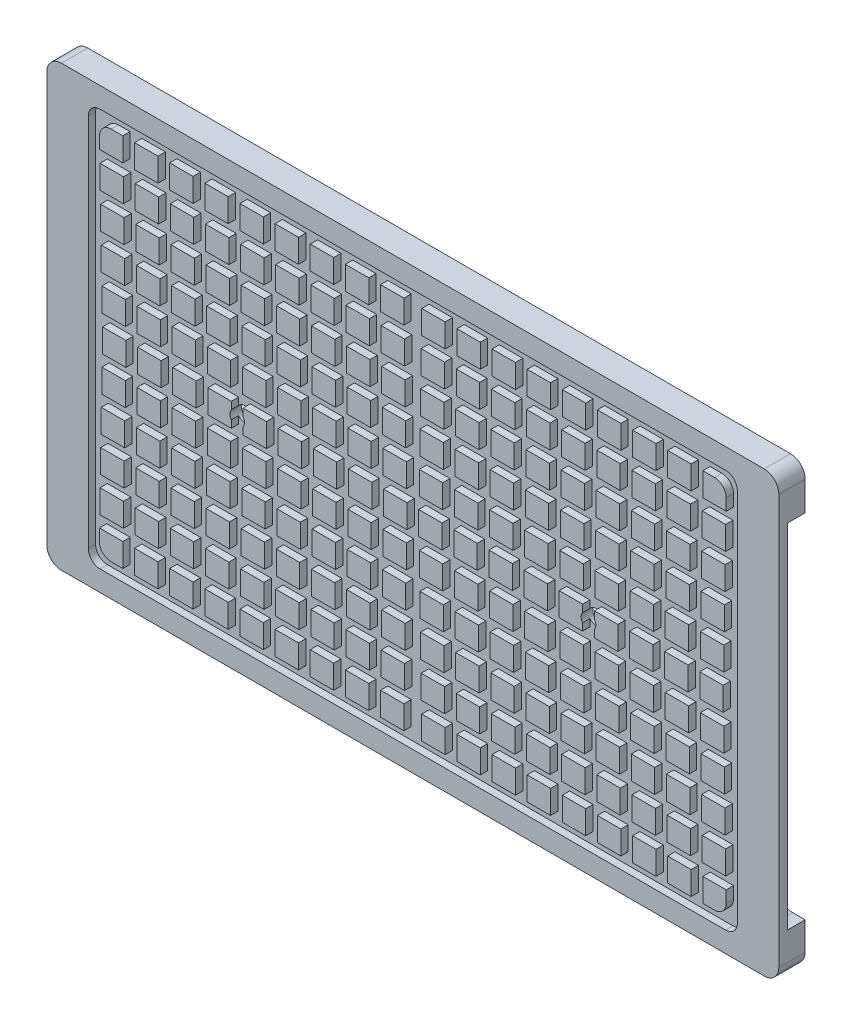
SolidWorks part; units mm, degrees
ref_plane "前视基准面" through (0, 0, 0) normal (0, 0, 1) x (1, 0, 0)
ref_plane "上视基准面" through (0, 0, 0) normal (0, 1, 0) x (1, 0, 0)
ref_plane "右视基准面" through (0, 0, 0) normal (1, 0, 0) x (0, 0, -1)
sketch "草图2" plane through (0, 0, 0) normal (0, 0, 1) x (1, 0, 0)
  line L1 (-120, 75) -> (120, 75)
  line L2 (-125, 70) -> (-125, -70)
  line L3 (-120, -75) -> (120, -75)
  line L4 (125, 70) -> (125, -70)
  line L5 (-125, 75) -> (125, -75) construction
  line L6 (-125, -75) -> (125, 75) construction
  arc A0 (125, 70) -> (120, 75) centre (120, 70) ccw
  arc A1 (125, -70) -> (120, -75) centre (120, -70) cw
  arc A2 (-120, -75) -> (-125, -70) centre (-120, -70) cw
  arc A3 (-125, 70) -> (-120, 75) centre (-120, 70) cw
  point P0 (0, 0)
  dimension "D3" = 5
  dimension "D1" = 250
  dimension "D2" = 150
extrude "凸台-拉伸1" add sketch "草图2" along normal blind 9
sketch "草图3" plane through (0, 0, 0) normal (0, 0, -1) x (-1, 0, 0)
  line L10 (-100, 65) -> (100, 65) construction
  line L11 (-99.2533, 65) -> (99.2533, 65)
  line L12 (-105, 59.2533) -> (-105, -59.2533)
  line L13 (-99.2533, -65) -> (99.2533, -65)
  line L14 (105, 59.2533) -> (105, -59.2533)
  line L15 (-105, 65) -> (105, -65) construction
  line L16 (-105, -65) -> (105, 65) construction
  line L17 (-105, -60) -> (-105, 60) construction
  line L18 (-99.2533, 67) -> (99.2533, 67)
  line L19 (107, 59.2533) -> (107, -59.2533)
  line L20 (-99.2533, -67) -> (99.2533, -67)
  line L21 (-107, 59.2533) -> (-107, -59.2533)
  line L22 (-106.0527, 63.2995) -> (103.9473, -66.7005) construction
  line L23 (-103.9473, -66.7005) -> (106.0527, 63.2995) construction
  arc A8 (105, 59.2533) -> (99.2533, 65) centre (99.2533, 59.2533) ccw
  arc A9 (105, -59.2533) -> (99.2533, -65) centre (99.2533, -59.2533) cw
  arc A10 (-105, -59.2533) -> (-99.2533, -65) centre (-99.2533, -59.2533) ccw
  arc A11 (-105, 59.2533) -> (-99.2533, 65) centre (-99.2533, 59.2533) cw
  arc A12 (107, 59.2533) -> (99.2533, 67) centre (99.2533, 59.2533) ccw
  arc A13 (107, -59.2533) -> (99.2533, -67) centre (99.2533, -59.2533) cw
  arc A14 (-107, -59.2533) -> (-99.2533, -67) centre (-99.2533, -59.2533) ccw
  arc A15 (-107, 59.2533) -> (-99.2533, 67) centre (-99.2533, 59.2533) cw
  point P0 (0, 0)
  dimension "D2" = 0
  dimension "D3" = 5.7467
  dimension "D1" = 0
  dimension "D4" = 2
extrude "凸台-拉伸2" add sketch "草图3" along normal blind 0.6
sketch "草图4" plane through (0, 0, 0) normal (0, 0, -1) x (-1, 0, 0)
  line L0 (125, 70) -> (125, -70) construction
  line L1 (125, -60.3809) -> (120.7467, -60.3809)
  line L2 (125, -60.3809) -> (125, 60)
  line L3 (125, 60) -> (120.7467, 60)
  line L4 (115, -54.6342) -> (115, 54.2533)
  line L5 (115, -55) -> (115, 55) construction
  line L6 (0, 0) -> (0, 16.1267) construction
  line L7 (-115, -54.6342) -> (-115, 54.2533)
  line L8 (-125, 60) -> (-120.7467, 60)
  line L9 (-125, -60.3809) -> (-125, 60)
  line L10 (-125, -60.3809) -> (-120.7467, -60.3809)
  arc A0 (115, -54.6342) -> (120.7467, -60.3809) centre (120.7467, -54.6342) ccw
  arc A1 (120.7467, 60) -> (115, 54.2533) centre (120.7467, 54.2533) ccw
  arc A2 (-120.7467, 60) -> (-115, 54.2533) centre (-120.7467, 54.2533) cw
  arc A3 (-115, -54.6342) -> (-120.7467, -60.3809) centre (-120.7467, -54.6342) cw
  dimension "D2" = 5.7467
  dimension "D1" = 0
extrude "切除-拉伸1" cut sketch "草图4" against normal blind 6 contours L7 A2 L8 L9 L10 A3 | L4 A1 L3 L2 L1 A0
sketch "草图5" plane through (0, -75, 0) normal (0, -1, 0) x (1, 0, 0)
  line L0 (0, 0) -> (0, 17.4603) construction
  line L1 (-120, 0) -> (120, 0) construction
  circle A0 centre (-15, 3.5) radius 2.25
  circle A1 centre (15, 3.5) radius 2.25
  dimension "D1" = 4.5
  dimension "D2" = 3.5
  dimension "D3" = 15
extrude "切除-拉伸2" cut sketch "草图5" against normal blind 15 contours A0 | A1
sketch "草图7" plane through (0, 0, 0) normal (0, 0, -1) x (-1, 0, 0)
  line L0 (0, 0) -> (-11.7747, 0) construction
  line L1 (0, 0) -> (0, -10.772) construction
  circle A0 centre (60, 0) radius 2.5
  circle A1 centre (-60, 0) radius 2.5
  dimension "D1" = 5
  dimension "D2" = 5
  dimension "D3" = 60
  dimension "D4" = 60
extrude "切除-拉伸3" cut sketch "草图7" against normal blind 15
sketch "草图8" plane through (0, 0, 0) normal (0, 0, -1) x (-1, 0, 0)
  line L0 (0, -0.8411) -> (0, -18.4077) construction
  line L3 (7.089, 60) -> (95.911, 60)
  line L22 (-99.2533, -65) -> (99.2533, -65) construction
  line L23 (-95, 60) -> (-7.089, 60)
  line L24 (-100, 55) -> (-100, -55)
  line L25 (-95, -60) -> (-7.089, -60)
  line L26 (100, 55.911) -> (100, -55)
  line L27 (-100, 60) -> (100, -60) construction
  line L28 (-100, -60) -> (100, 60) construction
  line L29 (105, -59.2533) -> (105, 59.2533) construction
  line L30 (99.2533, 65) -> (-99.2533, 65) construction
  line L31 (-105, 59.2533) -> (-105, -59.2533) construction
  line L33 (-3, 55.911) -> (-3, -55.911)
  line L35 (3, 55.911) -> (3, -55.911)
  line L36 (7.089, -60) -> (95, -60)
  arc A0 (7.089, 60) -> (3, 55.911) centre (7.089, 55.911) ccw
  arc A13 (100, -55) -> (95, -60) centre (95, -55) cw
  arc A14 (-100, -55) -> (-95, -60) centre (-95, -55) ccw
  arc A15 (-95, 60) -> (-100, 55) centre (-95, 55) ccw
  arc A16 (7.089, -60) -> (3, -55.911) centre (7.089, -55.911) cw
  arc A17 (-3, -55.911) -> (-7.089, -60) centre (-7.089, -55.911) cw
  arc A18 (-3, 55.911) -> (-7.089, 60) centre (-7.089, 55.911) ccw
  arc A19 (100, 55.911) -> (95.911, 60) centre (95.911, 55.911) ccw
  point P27 (3, -60)
  circle M1 centre (60, 0) radius 2.5
  circle M2 centre (-60, 0) radius 2.5
  dimension "D6" = 3
  dimension "D2" = 5
  dimension "D5" = 5
  dimension "D8" = 4.089
  dimension "D9" = 4.089
  dimension "D1" = 5
  dimension "D3" = 5
  dimension "D4" = 5
  dimension "D7" = 3
extrude "切除-拉伸4" cut sketch "草图8" against normal blind 5 contours M1 | M2 region at (-51.4784, 0.009, 0) region at (51.4712, 0, 0)
sketch "草图9" plane through (0, 0, 9) normal (0, 0, 1) x (1, 0, 0)
  line L0 (0, 0) -> (0, 17.992) construction
  line L1 (0, 0) -> (-10.173, 0) construction
  line L2 (-14, -4) -> (-22, -4)
  line L3 (-2, -4) -> (-10, -4)
  line L4 (-2, -4) -> (-2, 4)
  line L5 (-2, 4) -> (-10, 4)
  line L6 (-10, -4) -> (-10, 4)
  line L7 (-2, -4) -> (-10, 4) construction
  line L8 (-2, 4) -> (-10, -4) construction
  line L9 (-14, -4) -> (-14, 4)
  line L10 (-14, 4) -> (-22, 4)
  line L11 (-22, -4) -> (-22, 4)
  line L12 (-14, -4) -> (-22, 4) construction
  line L13 (-14, 4) -> (-22, -4) construction
  line L14 (-26, -4) -> (-34, -4)
  line L15 (-26, -4) -> (-26, 4)
  line L16 (-26, 4) -> (-34, 4)
  line L17 (-34, -4) -> (-34, 4)
  line L18 (-26, -4) -> (-34, 4) construction
  line L19 (-26, 4) -> (-34, -4) construction
  line L20 (-38, -4) -> (-46, -4)
  line L21 (-38, -4) -> (-38, 4)
  line L22 (-38, 4) -> (-46, 4)
  line L23 (-46, -4) -> (-46, 4)
  line L24 (-38, -4) -> (-46, 4) construction
  line L25 (-38, 4) -> (-46, -4) construction
  line L26 (-50, -4) -> (-58, -4)
  line L27 (-50, -4) -> (-50, 4)
  line L28 (-50, 4) -> (-58, 4)
  line L29 (-58, -4) -> (-58, -1.5)
  line L30 (-50, -4) -> (-58, 4) construction
  line L31 (-50, 4) -> (-58, -4) construction
  line L32 (-62, -4) -> (-70, -4)
  line L33 (-62, -4) -> (-62, -1.5)
  line L34 (-62, 4) -> (-70, 4)
  line L35 (-70, -4) -> (-70, 4)
  line L36 (-62, -4) -> (-70, 4) construction
  line L37 (-62, 4) -> (-70, -4) construction
  line L38 (-74, -4) -> (-82, -4)
  line L39 (-74, -4) -> (-74, 4)
  line L40 (-74, 4) -> (-82, 4)
  line L41 (-82, -4) -> (-82, 4)
  line L42 (-74, -4) -> (-82, 4) construction
  line L43 (-74, 4) -> (-82, -4) construction
  line L44 (-86, -4) -> (-94, -4)
  line L45 (-86, -4) -> (-86, 4)
  line L46 (-86, 4) -> (-94, 4)
  line L47 (-94, -4) -> (-94, 4)
  line L48 (-86, -4) -> (-94, 4) construction
  line L49 (-86, 4) -> (-94, -4) construction
  line L50 (-98, -4) -> (-106, -4)
  line L51 (-98, -4) -> (-98, 4)
  line L52 (-98, 4) -> (-106, 4)
  line L53 (-106, -4) -> (-106, 4)
  line L54 (-98, -4) -> (-106, 4) construction
  line L55 (-98, 4) -> (-106, -4) construction
  line L56 (-14.2094, 7.9982) -> (-22.2094, 7.9982)
  line L57 (-14.2094, 7.9982) -> (-14.2094, 15.9982)
  line L58 (-14.2094, 15.9982) -> (-22.2094, 15.9982)
  line L59 (-22.2094, 7.9982) -> (-22.2094, 15.9982)
  line L60 (-14.2094, 7.9982) -> (-22.2094, 15.9982) construction
  line L61 (-14.2094, 15.9982) -> (-22.2094, 7.9982) construction
  line L62 (-26.2094, 7.9982) -> (-34.2094, 7.9982)
  line L63 (-26.2094, 7.9982) -> (-26.2094, 15.9982)
  line L64 (-26.2094, 15.9982) -> (-34.2094, 15.9982)
  line L65 (-34.2094, 7.9982) -> (-34.2094, 15.9982)
  line L66 (-26.2094, 7.9982) -> (-34.2094, 15.9982) construction
  line L67 (-26.2094, 15.9982) -> (-34.2094, 7.9982) construction
  line L68 (-38.2094, 7.9982) -> (-46.2094, 7.9982)
  line L69 (-38.2094, 7.9982) -> (-38.2094, 15.9982)
  line L70 (-38.2094, 15.9982) -> (-46.2094, 15.9982)
  line L71 (-46.2094, 7.9982) -> (-46.2094, 15.9982)
  line L72 (-38.2094, 7.9982) -> (-46.2094, 15.9982) construction
  line L73 (-38.2094, 15.9982) -> (-46.2094, 7.9982) construction
  line L74 (-50.2094, 7.9982) -> (-58.2094, 7.9982)
  line L75 (-50.2094, 7.9982) -> (-50.2094, 15.9982)
  line L76 (-50.2094, 15.9982) -> (-58.2094, 15.9982)
  line L77 (-58.2094, 7.9982) -> (-58.2094, 15.9982)
  line L78 (-50.2094, 7.9982) -> (-58.2094, 15.9982) construction
  line L79 (-50.2094, 15.9982) -> (-58.2094, 7.9982) construction
  line L80 (-62.2094, 7.9982) -> (-70.2094, 7.9982)
  line L81 (-62.2094, 7.9982) -> (-62.2094, 15.9982)
  line L82 (-62.2094, 15.9982) -> (-70.2094, 15.9982)
  line L83 (-70.2094, 7.9982) -> (-70.2094, 15.9982)
  line L84 (-62.2094, 7.9982) -> (-70.2094, 15.9982) construction
  line L85 (-62.2094, 15.9982) -> (-70.2094, 7.9982) construction
  line L86 (-74.2094, 7.9982) -> (-82.2094, 7.9982)
  line L87 (-74.2094, 7.9982) -> (-74.2094, 15.9982)
  line L88 (-74.2094, 15.9982) -> (-82.2094, 15.9982)
  line L89 (-82.2094, 7.9982) -> (-82.2094, 15.9982)
  line L90 (-74.2094, 7.9982) -> (-82.2094, 15.9982) construction
  line L91 (-74.2094, 15.9982) -> (-82.2094, 7.9982) construction
  line L92 (-86.2094, 7.9982) -> (-94.2094, 7.9982)
  line L93 (-86.2094, 7.9982) -> (-86.2094, 15.9982)
  line L94 (-86.2094, 15.9982) -> (-94.2094, 15.9982)
  line L95 (-94.2094, 7.9982) -> (-94.2094, 15.9982)
  line L96 (-86.2094, 7.9982) -> (-94.2094, 15.9982) construction
  line L97 (-86.2094, 15.9982) -> (-94.2094, 7.9982) construction
  line L98 (-98.2094, 7.9982) -> (-106.2094, 7.9982)
  line L99 (-98.2094, 7.9982) -> (-98.2094, 15.9982)
  line L100 (-98.2094, 15.9982) -> (-106.2094, 15.9982)
  line L101 (-106.2094, 7.9982) -> (-106.2094, 15.9982)
  line L102 (-98.2094, 7.9982) -> (-106.2094, 15.9982) construction
  line L103 (-98.2094, 15.9982) -> (-106.2094, 7.9982) construction
  line L104 (-14.4189, 19.9963) -> (-22.4189, 19.9963)
  line L105 (-14.4189, 19.9963) -> (-14.4189, 27.9963)
  line L106 (-14.4189, 27.9963) -> (-22.4189, 27.9963)
  line L107 (-22.4189, 19.9963) -> (-22.4189, 27.9963)
  line L108 (-14.4189, 19.9963) -> (-22.4189, 27.9963) construction
  line L109 (-14.4189, 27.9963) -> (-22.4189, 19.9963) construction
  line L110 (-26.4189, 19.9963) -> (-34.4189, 19.9963)
  line L111 (-26.4189, 19.9963) -> (-26.4189, 27.9963)
  line L112 (-26.4189, 27.9963) -> (-34.4189, 27.9963)
  line L113 (-34.4189, 19.9963) -> (-34.4189, 27.9963)
  line L114 (-26.4189, 19.9963) -> (-34.4189, 27.9963) construction
  line L115 (-26.4189, 27.9963) -> (-34.4189, 19.9963) construction
  line L116 (-38.4189, 19.9963) -> (-46.4189, 19.9963)
  line L117 (-38.4189, 19.9963) -> (-38.4189, 27.9963)
  line L118 (-38.4189, 27.9963) -> (-46.4189, 27.9963)
  line L119 (-46.4189, 19.9963) -> (-46.4189, 27.9963)
  line L120 (-38.4189, 19.9963) -> (-46.4189, 27.9963) construction
  line L121 (-38.4189, 27.9963) -> (-46.4189, 19.9963) construction
  line L122 (-50.4189, 19.9963) -> (-58.4189, 19.9963)
  line L123 (-50.4189, 19.9963) -> (-50.4189, 27.9963)
  line L124 (-50.4189, 27.9963) -> (-58.4189, 27.9963)
  line L125 (-58.4189, 19.9963) -> (-58.4189, 27.9963)
  line L126 (-50.4189, 19.9963) -> (-58.4189, 27.9963) construction
  line L127 (-50.4189, 27.9963) -> (-58.4189, 19.9963) construction
  line L128 (-62.4189, 19.9963) -> (-70.4189, 19.9963)
  line L129 (-62.4189, 19.9963) -> (-62.4189, 27.9963)
  line L130 (-62.4189, 27.9963) -> (-70.4189, 27.9963)
  line L131 (-70.4189, 19.9963) -> (-70.4189, 27.9963)
  line L132 (-62.4189, 19.9963) -> (-70.4189, 27.9963) construction
  line L133 (-62.4189, 27.9963) -> (-70.4189, 19.9963) construction
  line L134 (-74.4189, 19.9963) -> (-82.4189, 19.9963)
  line L135 (-74.4189, 19.9963) -> (-74.4189, 27.9963)
  line L136 (-74.4189, 27.9963) -> (-82.4189, 27.9963)
  line L137 (-82.4189, 19.9963) -> (-82.4189, 27.9963)
  line L138 (-74.4189, 19.9963) -> (-82.4189, 27.9963) construction
  line L139 (-74.4189, 27.9963) -> (-82.4189, 19.9963) construction
  line L140 (-86.4189, 19.9963) -> (-94.4189, 19.9963)
  line L141 (-86.4189, 19.9963) -> (-86.4189, 27.9963)
  line L142 (-86.4189, 27.9963) -> (-94.4189, 27.9963)
  line L143 (-94.4189, 19.9963) -> (-94.4189, 27.9963)
  line L144 (-86.4189, 19.9963) -> (-94.4189, 27.9963) construction
  line L145 (-86.4189, 27.9963) -> (-94.4189, 19.9963) construction
  line L146 (-98.4189, 19.9963) -> (-106.4189, 19.9963)
  line L147 (-98.4189, 19.9963) -> (-98.4189, 27.9963)
  line L148 (-98.4189, 27.9963) -> (-106.4189, 27.9963)
  line L149 (-106.4189, 19.9963) -> (-106.4189, 27.9963)
  line L150 (-98.4189, 19.9963) -> (-106.4189, 27.9963) construction
  line L151 (-98.4189, 27.9963) -> (-106.4189, 19.9963) construction
  line L152 (-14.6283, 31.9945) -> (-22.6283, 31.9945)
  line L153 (-14.6283, 31.9945) -> (-14.6283, 39.9945)
  line L154 (-14.6283, 39.9945) -> (-22.6283, 39.9945)
  line L155 (-22.6283, 31.9945) -> (-22.6283, 39.9945)
  line L156 (-14.6283, 31.9945) -> (-22.6283, 39.9945) construction
  line L157 (-14.6283, 39.9945) -> (-22.6283, 31.9945) construction
  line L158 (-26.6283, 31.9945) -> (-34.6283, 31.9945)
  line L159 (-26.6283, 31.9945) -> (-26.6283, 39.9945)
  line L160 (-26.6283, 39.9945) -> (-34.6283, 39.9945)
  line L161 (-34.6283, 31.9945) -> (-34.6283, 39.9945)
  line L162 (-26.6283, 31.9945) -> (-34.6283, 39.9945) construction
  line L163 (-26.6283, 39.9945) -> (-34.6283, 31.9945) construction
  line L164 (-38.6283, 31.9945) -> (-46.6283, 31.9945)
  line L165 (-38.6283, 31.9945) -> (-38.6283, 39.9945)
  line L166 (-38.6283, 39.9945) -> (-46.6283, 39.9945)
  line L167 (-46.6283, 31.9945) -> (-46.6283, 39.9945)
  line L168 (-38.6283, 31.9945) -> (-46.6283, 39.9945) construction
  line L169 (-38.6283, 39.9945) -> (-46.6283, 31.9945) construction
  line L170 (-50.6283, 31.9945) -> (-58.6283, 31.9945)
  line L171 (-50.6283, 31.9945) -> (-50.6283, 39.9945)
  line L172 (-50.6283, 39.9945) -> (-58.6283, 39.9945)
  line L173 (-58.6283, 31.9945) -> (-58.6283, 39.9945)
  line L174 (-50.6283, 31.9945) -> (-58.6283, 39.9945) construction
  line L175 (-50.6283, 39.9945) -> (-58.6283, 31.9945) construction
  line L176 (-62.6283, 31.9945) -> (-70.6283, 31.9945)
  line L177 (-62.6283, 31.9945) -> (-62.6283, 39.9945)
  line L178 (-62.6283, 39.9945) -> (-70.6283, 39.9945)
  line L179 (-70.6283, 31.9945) -> (-70.6283, 39.9945)
  line L180 (-62.6283, 31.9945) -> (-70.6283, 39.9945) construction
  line L181 (-62.6283, 39.9945) -> (-70.6283, 31.9945) construction
  line L182 (-74.6283, 31.9945) -> (-82.6283, 31.9945)
  line L183 (-74.6283, 31.9945) -> (-74.6283, 39.9945)
  line L184 (-74.6283, 39.9945) -> (-82.6283, 39.9945)
  line L185 (-82.6283, 31.9945) -> (-82.6283, 39.9945)
  line L186 (-74.6283, 31.9945) -> (-82.6283, 39.9945) construction
  line L187 (-74.6283, 39.9945) -> (-82.6283, 31.9945) construction
  line L188 (-86.6283, 31.9945) -> (-94.6283, 31.9945)
  line L189 (-86.6283, 31.9945) -> (-86.6283, 39.9945)
  line L190 (-86.6283, 39.9945) -> (-94.6283, 39.9945)
  line L191 (-94.6283, 31.9945) -> (-94.6283, 39.9945)
  line L192 (-86.6283, 31.9945) -> (-94.6283, 39.9945) construction
  line L193 (-86.6283, 39.9945) -> (-94.6283, 31.9945) construction
  line L194 (-98.6283, 31.9945) -> (-106.6283, 31.9945)
  line L195 (-98.6283, 31.9945) -> (-98.6283, 39.9945)
  line L196 (-98.6283, 39.9945) -> (-106.6283, 39.9945)
  line L197 (-106.6283, 31.9945) -> (-106.6283, 39.9945)
  line L198 (-98.6283, 31.9945) -> (-106.6283, 39.9945) construction
  line L199 (-98.6283, 39.9945) -> (-106.6283, 31.9945) construction
  line L200 (-14.8377, 43.9927) -> (-22.8377, 43.9927)
  line L201 (-14.8377, 43.9927) -> (-14.8377, 51.9927)
  line L202 (-14.8377, 51.9927) -> (-22.8377, 51.9927)
  line L203 (-22.8377, 43.9927) -> (-22.8377, 51.9927)
  line L204 (-14.8377, 43.9927) -> (-22.8377, 51.9927) construction
  line L205 (-14.8377, 51.9927) -> (-22.8377, 43.9927) construction
  line L206 (-26.8377, 43.9927) -> (-34.8377, 43.9927)
  line L207 (-26.8377, 43.9927) -> (-26.8377, 51.9927)
  line L208 (-26.8377, 51.9927) -> (-34.8377, 51.9927)
  line L209 (-34.8377, 43.9927) -> (-34.8377, 51.9927)
  line L210 (-26.8377, 43.9927) -> (-34.8377, 51.9927) construction
  line L211 (-26.8377, 51.9927) -> (-34.8377, 43.9927) construction
  line L212 (-38.8377, 43.9927) -> (-46.8377, 43.9927)
  line L213 (-38.8377, 43.9927) -> (-38.8377, 51.9927)
  line L214 (-38.8377, 51.9927) -> (-46.8377, 51.9927)
  line L215 (-46.8377, 43.9927) -> (-46.8377, 51.9927)
  line L216 (-38.8377, 43.9927) -> (-46.8377, 51.9927) construction
  line L217 (-38.8377, 51.9927) -> (-46.8377, 43.9927) construction
  line L218 (-50.8377, 43.9927) -> (-58.8377, 43.9927)
  line L219 (-50.8377, 43.9927) -> (-50.8377, 51.9927)
  line L220 (-50.8377, 51.9927) -> (-58.8377, 51.9927)
  line L221 (-58.8377, 43.9927) -> (-58.8377, 51.9927)
  line L222 (-50.8377, 43.9927) -> (-58.8377, 51.9927) construction
  line L223 (-50.8377, 51.9927) -> (-58.8377, 43.9927) construction
  line L224 (-62.8377, 43.9927) -> (-70.8377, 43.9927)
  line L225 (-62.8377, 43.9927) -> (-62.8377, 51.9927)
  line L226 (-62.8377, 51.9927) -> (-70.8377, 51.9927)
  line L227 (-70.8377, 43.9927) -> (-70.8377, 51.9927)
  line L228 (-62.8377, 43.9927) -> (-70.8377, 51.9927) construction
  line L229 (-62.8377, 51.9927) -> (-70.8377, 43.9927) construction
  line L230 (-74.8377, 43.9927) -> (-82.8377, 43.9927)
  line L231 (-74.8377, 43.9927) -> (-74.8377, 51.9927)
  line L232 (-74.8377, 51.9927) -> (-82.8377, 51.9927)
  line L233 (-82.8377, 43.9927) -> (-82.8377, 51.9927)
  line L234 (-74.8377, 43.9927) -> (-82.8377, 51.9927) construction
  line L235 (-74.8377, 51.9927) -> (-82.8377, 43.9927) construction
  line L236 (-86.8377, 43.9927) -> (-94.8377, 43.9927)
  line L237 (-86.8377, 43.9927) -> (-86.8377, 51.9927)
  line L238 (-86.8377, 51.9927) -> (-94.8377, 51.9927)
  line L239 (-94.8377, 43.9927) -> (-94.8377, 51.9927)
  line L240 (-86.8377, 43.9927) -> (-94.8377, 51.9927) construction
  line L241 (-86.8377, 51.9927) -> (-94.8377, 43.9927) construction
  line L242 (-98.8377, 43.9927) -> (-106.8377, 43.9927)
  line L243 (-98.8377, 43.9927) -> (-98.8377, 51.9927)
  line L244 (-98.8377, 51.9927) -> (-106.8377, 51.9927)
  line L245 (-106.8377, 43.9927) -> (-106.8377, 51.9927)
  line L246 (-98.8377, 43.9927) -> (-106.8377, 51.9927) construction
  line L247 (-98.8377, 51.9927) -> (-106.8377, 43.9927) construction
  line L248 (-15.0471, 55.9909) -> (-23.0471, 55.9909)
  line L249 (-15.0471, 55.9909) -> (-15.0471, 63.9909)
  line L250 (-15.0471, 63.9909) -> (-23.0471, 63.9909)
  line L251 (-23.0471, 55.9909) -> (-23.0471, 63.9909)
  line L252 (-15.0471, 55.9909) -> (-23.0471, 63.9909) construction
  line L253 (-15.0471, 63.9909) -> (-23.0471, 55.9909) construction
  line L254 (-27.0471, 55.9909) -> (-35.0471, 55.9909)
  line L255 (-27.0471, 55.9909) -> (-27.0471, 63.9909)
  line L256 (-27.0471, 63.9909) -> (-35.0471, 63.9909)
  line L257 (-35.0471, 55.9909) -> (-35.0471, 63.9909)
  line L258 (-27.0471, 55.9909) -> (-35.0471, 63.9909) construction
  line L259 (-27.0471, 63.9909) -> (-35.0471, 55.9909) construction
  line L260 (-39.0471, 55.9909) -> (-47.0471, 55.9909)
  line L261 (-39.0471, 55.9909) -> (-39.0471, 63.9909)
  line L262 (-39.0471, 63.9909) -> (-47.0471, 63.9909)
  line L263 (-47.0471, 55.9909) -> (-47.0471, 63.9909)
  line L264 (-39.0471, 55.9909) -> (-47.0471, 63.9909) construction
  line L265 (-39.0471, 63.9909) -> (-47.0471, 55.9909) construction
  line L266 (-51.0471, 55.9909) -> (-59.0471, 55.9909)
  line L267 (-51.0471, 55.9909) -> (-51.0471, 63.9909)
  line L268 (-51.0471, 63.9909) -> (-59.0471, 63.9909)
  line L269 (-59.0471, 55.9909) -> (-59.0471, 63.9909)
  line L270 (-51.0471, 55.9909) -> (-59.0471, 63.9909) construction
  line L271 (-51.0471, 63.9909) -> (-59.0471, 55.9909) construction
  line L272 (-63.0471, 55.9909) -> (-71.0471, 55.9909)
  line L273 (-63.0471, 55.9909) -> (-63.0471, 63.9909)
  line L274 (-63.0471, 63.9909) -> (-71.0471, 63.9909)
  line L275 (-71.0471, 55.9909) -> (-71.0471, 63.9909)
  line L276 (-63.0471, 55.9909) -> (-71.0471, 63.9909) construction
  line L277 (-63.0471, 63.9909) -> (-71.0471, 55.9909) construction
  line L278 (-75.0471, 55.9909) -> (-83.0471, 55.9909)
  line L279 (-75.0471, 55.9909) -> (-75.0471, 63.9909)
  line L280 (-75.0471, 63.9909) -> (-83.0471, 63.9909)
  line L281 (-83.0471, 55.9909) -> (-83.0471, 63.9909)
  line L282 (-75.0471, 55.9909) -> (-83.0471, 63.9909) construction
  line L283 (-75.0471, 63.9909) -> (-83.0471, 55.9909) construction
  line L284 (-87.0471, 55.9909) -> (-95.0471, 55.9909)
  line L285 (-87.0471, 55.9909) -> (-87.0471, 63.9909)
  line L286 (-87.0471, 63.9909) -> (-95.0471, 63.9909)
  line L287 (-95.0471, 55.9909) -> (-95.0471, 63.9909)
  line L288 (-87.0471, 55.9909) -> (-95.0471, 63.9909) construction
  line L289 (-87.0471, 63.9909) -> (-95.0471, 55.9909) construction
  line L290 (-99.0471, 55.9909) -> (-107.0471, 55.9909)
  line L291 (-99.0471, 55.9909) -> (-99.0471, 63.9909)
  line L292 (-99.0471, 63.9909) -> (-103.0471, 63.9909)
  line L293 (-107.0471, 55.9909) -> (-107.0471, 59.9909)
  line L294 (-99.0471, 55.9909) -> (-107.0471, 63.9909) construction
  line L295 (-99.0471, 63.9909) -> (-107.0471, 55.9909) construction
  line L296 (-2.2094, 7.9982) -> (-10.2094, 7.9982)
  line L297 (-2.2094, 7.9982) -> (-2.2094, 15.9982)
  line L298 (-2.2094, 15.9982) -> (-10.2094, 15.9982)
  line L299 (-10.2094, 7.9982) -> (-10.2094, 15.9982)
  line L300 (-2.2094, 7.9982) -> (-10.2094, 15.9982) construction
  line L301 (-2.2094, 15.9982) -> (-10.2094, 7.9982) construction
  line L302 (-2.4189, 19.9963) -> (-10.4189, 19.9963)
  line L303 (-2.4189, 19.9963) -> (-2.4189, 27.9963)
  line L304 (-2.4189, 27.9963) -> (-10.4189, 27.9963)
  line L305 (-10.4189, 19.9963) -> (-10.4189, 27.9963)
  line L306 (-2.4189, 19.9963) -> (-10.4189, 27.9963) construction
  line L307 (-2.4189, 27.9963) -> (-10.4189, 19.9963) construction
  line L308 (-2.6283, 31.9945) -> (-10.6283, 31.9945)
  line L309 (-2.6283, 31.9945) -> (-2.6283, 39.9945)
  line L310 (-2.6283, 39.9945) -> (-10.6283, 39.9945)
  line L311 (-10.6283, 31.9945) -> (-10.6283, 39.9945)
  line L312 (-2.6283, 31.9945) -> (-10.6283, 39.9945) construction
  line L313 (-2.6283, 39.9945) -> (-10.6283, 31.9945) construction
  line L314 (-2.8377, 43.9927) -> (-10.8377, 43.9927)
  line L315 (-2.8377, 43.9927) -> (-2.8377, 51.9927)
  line L316 (-2.8377, 51.9927) -> (-10.8377, 51.9927)
  line L317 (-10.8377, 43.9927) -> (-10.8377, 51.9927)
  line L318 (-2.8377, 43.9927) -> (-10.8377, 51.9927) construction
  line L319 (-2.8377, 51.9927) -> (-10.8377, 43.9927) construction
  line L320 (-3.0471, 55.9909) -> (-11.0471, 55.9909)
  line L321 (-3.0471, 55.9909) -> (-3.0471, 63.9909)
  line L322 (-3.0471, 63.9909) -> (-11.0471, 63.9909)
  line L323 (-11.0471, 55.9909) -> (-11.0471, 63.9909)
  line L324 (-3.0471, 55.9909) -> (-11.0471, 63.9909) construction
  line L325 (-3.0471, 63.9909) -> (-11.0471, 55.9909) construction
  line L326 (-6, 0) -> (-18, 0) construction
  line L327 (-6, 0) -> (-6.2094, 11.9982) construction
  line L328 (6, 0) -> (6.2094, 11.9982) construction
  line L329 (6, 0) -> (18, 0) construction
  line L330 (3.0471, 63.9909) -> (11.0471, 55.9909) construction
  line L331 (3.0471, 55.9909) -> (11.0471, 63.9909) construction
  line L332 (2.8377, 51.9927) -> (10.8377, 43.9927) construction
  line L333 (2.8377, 43.9927) -> (10.8377, 51.9927) construction
  line L334 (2.6283, 39.9945) -> (10.6283, 31.9945) construction
  line L335 (2.6283, 31.9945) -> (10.6283, 39.9945) construction
  line L336 (2.4189, 27.9963) -> (10.4189, 19.9963) construction
  line L337 (2.4189, 19.9963) -> (10.4189, 27.9963) construction
  line L338 (2.2094, 15.9982) -> (10.2094, 7.9982) construction
  line L339 (2.2094, 7.9982) -> (10.2094, 15.9982) construction
  line L340 (99.0471, 63.9909) -> (107.0471, 55.9909) construction
  line L341 (99.0471, 55.9909) -> (107.0471, 63.9909) construction
  line L342 (87.0471, 63.9909) -> (95.0471, 55.9909) construction
  line L343 (87.0471, 55.9909) -> (95.0471, 63.9909) construction
  line L344 (75.0471, 63.9909) -> (83.0471, 55.9909) construction
  line L345 (75.0471, 55.9909) -> (83.0471, 63.9909) construction
  line L346 (63.0471, 63.9909) -> (71.0471, 55.9909) construction
  line L347 (63.0471, 55.9909) -> (71.0471, 63.9909) construction
  line L348 (51.0471, 63.9909) -> (59.0471, 55.9909) construction
  line L349 (51.0471, 55.9909) -> (59.0471, 63.9909) construction
  line L350 (39.0471, 63.9909) -> (47.0471, 55.9909) construction
  line L351 (39.0471, 55.9909) -> (47.0471, 63.9909) construction
  line L352 (27.0471, 63.9909) -> (35.0471, 55.9909) construction
  line L353 (27.0471, 55.9909) -> (35.0471, 63.9909) construction
  line L354 (15.0471, 63.9909) -> (23.0471, 55.9909) construction
  line L355 (15.0471, 55.9909) -> (23.0471, 63.9909) construction
  line L356 (98.8377, 51.9927) -> (106.8377, 43.9927) construction
  line L357 (98.8377, 43.9927) -> (106.8377, 51.9927) construction
  line L358 (86.8377, 51.9927) -> (94.8377, 43.9927) construction
  line L359 (86.8377, 43.9927) -> (94.8377, 51.9927) construction
  line L360 (74.8377, 51.9927) -> (82.8377, 43.9927) construction
  line L361 (74.8377, 43.9927) -> (82.8377, 51.9927) construction
  line L362 (62.8377, 51.9927) -> (70.8377, 43.9927) construction
  line L363 (62.8377, 43.9927) -> (70.8377, 51.9927) construction
  line L364 (50.8377, 51.9927) -> (58.8377, 43.9927) construction
  line L365 (50.8377, 43.9927) -> (58.8377, 51.9927) construction
  line L366 (38.8377, 51.9927) -> (46.8377, 43.9927) construction
  line L367 (38.8377, 43.9927) -> (46.8377, 51.9927) construction
  line L368 (26.8377, 51.9927) -> (34.8377, 43.9927) construction
  line L369 (26.8377, 43.9927) -> (34.8377, 51.9927) construction
  line L370 (14.8377, 51.9927) -> (22.8377, 43.9927) construction
  line L371 (14.8377, 43.9927) -> (22.8377, 51.9927) construction
  line L372 (98.6283, 39.9945) -> (106.6283, 31.9945) construction
  line L373 (98.6283, 31.9945) -> (106.6283, 39.9945) construction
  line L374 (86.6283, 39.9945) -> (94.6283, 31.9945) construction
  line L375 (86.6283, 31.9945) -> (94.6283, 39.9945) construction
  line L376 (74.6283, 39.9945) -> (82.6283, 31.9945) construction
  line L377 (74.6283, 31.9945) -> (82.6283, 39.9945) construction
  line L378 (62.6283, 39.9945) -> (70.6283, 31.9945) construction
  line L379 (62.6283, 31.9945) -> (70.6283, 39.9945) construction
  line L380 (50.6283, 39.9945) -> (58.6283, 31.9945) construction
  line L381 (50.6283, 31.9945) -> (58.6283, 39.9945) construction
  line L382 (38.6283, 39.9945) -> (46.6283, 31.9945) construction
  line L383 (38.6283, 31.9945) -> (46.6283, 39.9945) construction
  line L384 (26.6283, 39.9945) -> (34.6283, 31.9945) construction
  line L385 (26.6283, 31.9945) -> (34.6283, 39.9945) construction
  line L386 (14.6283, 39.9945) -> (22.6283, 31.9945) construction
  line L387 (14.6283, 31.9945) -> (22.6283, 39.9945) construction
  line L388 (98.4189, 27.9963) -> (106.4189, 19.9963) construction
  line L389 (98.4189, 19.9963) -> (106.4189, 27.9963) construction
  line L390 (86.4189, 27.9963) -> (94.4189, 19.9963) construction
  line L391 (86.4189, 19.9963) -> (94.4189, 27.9963) construction
  line L392 (74.4189, 27.9963) -> (82.4189, 19.9963) construction
  line L393 (74.4189, 19.9963) -> (82.4189, 27.9963) construction
  line L394 (62.4189, 27.9963) -> (70.4189, 19.9963) construction
  line L395 (62.4189, 19.9963) -> (70.4189, 27.9963) construction
  line L396 (50.4189, 27.9963) -> (58.4189, 19.9963) construction
  line L397 (50.4189, 19.9963) -> (58.4189, 27.9963) construction
  line L398 (38.4189, 27.9963) -> (46.4189, 19.9963) construction
  line L399 (38.4189, 19.9963) -> (46.4189, 27.9963) construction
  line L400 (26.4189, 27.9963) -> (34.4189, 19.9963) construction
  line L401 (26.4189, 19.9963) -> (34.4189, 27.9963) construction
  line L402 (14.4189, 27.9963) -> (22.4189, 19.9963) construction
  line L403 (14.4189, 19.9963) -> (22.4189, 27.9963) construction
  line L404 (98.2094, 15.9982) -> (106.2094, 7.9982) construction
  line L405 (98.2094, 7.9982) -> (106.2094, 15.9982) construction
  line L406 (86.2094, 15.9982) -> (94.2094, 7.9982) construction
  line L407 (86.2094, 7.9982) -> (94.2094, 15.9982) construction
  line L408 (74.2094, 15.9982) -> (82.2094, 7.9982) construction
  line L409 (74.2094, 7.9982) -> (82.2094, 15.9982) construction
  line L410 (62.2094, 15.9982) -> (70.2094, 7.9982) construction
  line L411 (62.2094, 7.9982) -> (70.2094, 15.9982) construction
  line L412 (50.2094, 15.9982) -> (58.2094, 7.9982) construction
  line L413 (50.2094, 7.9982) -> (58.2094, 15.9982) construction
  line L414 (38.2094, 15.9982) -> (46.2094, 7.9982) construction
  line L415 (38.2094, 7.9982) -> (46.2094, 15.9982) construction
  line L416 (26.2094, 15.9982) -> (34.2094, 7.9982) construction
  line L417 (26.2094, 7.9982) -> (34.2094, 15.9982) construction
  line L418 (14.2094, 15.9982) -> (22.2094, 7.9982) construction
  line L419 (14.2094, 7.9982) -> (22.2094, 15.9982) construction
  line L420 (98, 4) -> (106, -4) construction
  line L421 (98, -4) -> (106, 4) construction
  line L422 (86, 4) -> (94, -4) construction
  line L423 (86, -4) -> (94, 4) construction
  line L424 (74, 4) -> (82, -4) construction
  line L425 (74, -4) -> (82, 4) construction
  line L426 (62, 4) -> (70, -4) construction
  line L427 (62, -4) -> (70, 4) construction
  line L428 (50, 4) -> (58, -4) construction
  line L429 (50, -4) -> (58, 4) construction
  line L430 (38, 4) -> (46, -4) construction
  line L431 (38, -4) -> (46, 4) construction
  line L432 (26, 4) -> (34, -4) construction
  line L433 (26, -4) -> (34, 4) construction
  line L434 (14, 4) -> (22, -4) construction
  line L435 (14, -4) -> (22, 4) construction
  line L436 (2, 4) -> (10, -4) construction
  line L437 (2, -4) -> (10, 4) construction
  line L438 (11.0471, 55.9909) -> (11.0471, 63.9909)
  line L439 (3.0471, 63.9909) -> (11.0471, 63.9909)
  line L440 (3.0471, 55.9909) -> (3.0471, 63.9909)
  line L441 (3.0471, 55.9909) -> (11.0471, 55.9909)
  line L442 (10.8377, 43.9927) -> (10.8377, 51.9927)
  line L443 (2.8377, 51.9927) -> (10.8377, 51.9927)
  line L444 (2.8377, 43.9927) -> (2.8377, 51.9927)
  line L445 (2.8377, 43.9927) -> (10.8377, 43.9927)
  line L446 (10.6283, 31.9945) -> (10.6283, 39.9945)
  line L447 (2.6283, 39.9945) -> (10.6283, 39.9945)
  line L448 (2.6283, 31.9945) -> (2.6283, 39.9945)
  line L449 (2.6283, 31.9945) -> (10.6283, 31.9945)
  line L450 (10.4189, 19.9963) -> (10.4189, 27.9963)
  line L451 (2.4189, 27.9963) -> (10.4189, 27.9963)
  line L452 (2.4189, 19.9963) -> (2.4189, 27.9963)
  line L453 (2.4189, 19.9963) -> (10.4189, 19.9963)
  line L454 (10.2094, 7.9982) -> (10.2094, 15.9982)
  line L455 (2.2094, 15.9982) -> (10.2094, 15.9982)
  line L456 (2.2094, 7.9982) -> (2.2094, 15.9982)
  line L457 (2.2094, 7.9982) -> (10.2094, 7.9982)
  line L458 (107.0471, 55.9909) -> (107.0471, 59.9909)
  line L459 (99.0471, 63.9909) -> (103.0471, 63.9909)
  line L460 (99.0471, 55.9909) -> (99.0471, 63.9909)
  line L461 (99.0471, 55.9909) -> (107.0471, 55.9909)
  line L462 (95.0471, 55.9909) -> (95.0471, 63.9909)
  line L463 (87.0471, 63.9909) -> (95.0471, 63.9909)
  line L464 (87.0471, 55.9909) -> (87.0471, 63.9909)
  line L465 (87.0471, 55.9909) -> (95.0471, 55.9909)
  line L466 (83.0471, 55.9909) -> (83.0471, 63.9909)
  line L467 (75.0471, 63.9909) -> (83.0471, 63.9909)
  line L468 (75.0471, 55.9909) -> (75.0471, 63.9909)
  line L469 (75.0471, 55.9909) -> (83.0471, 55.9909)
  line L470 (71.0471, 55.9909) -> (71.0471, 63.9909)
  line L471 (63.0471, 63.9909) -> (71.0471, 63.9909)
  line L472 (63.0471, 55.9909) -> (63.0471, 63.9909)
  line L473 (63.0471, 55.9909) -> (71.0471, 55.9909)
  line L474 (59.0471, 55.9909) -> (59.0471, 63.9909)
  line L475 (51.0471, 63.9909) -> (59.0471, 63.9909)
  line L476 (51.0471, 55.9909) -> (51.0471, 63.9909)
  line L477 (51.0471, 55.9909) -> (59.0471, 55.9909)
  line L478 (47.0471, 55.9909) -> (47.0471, 63.9909)
  line L479 (39.0471, 63.9909) -> (47.0471, 63.9909)
  line L480 (39.0471, 55.9909) -> (39.0471, 63.9909)
  line L481 (39.0471, 55.9909) -> (47.0471, 55.9909)
  line L482 (35.0471, 55.9909) -> (35.0471, 63.9909)
  line L483 (27.0471, 63.9909) -> (35.0471, 63.9909)
  line L484 (27.0471, 55.9909) -> (27.0471, 63.9909)
  line L485 (27.0471, 55.9909) -> (35.0471, 55.9909)
  line L486 (23.0471, 55.9909) -> (23.0471, 63.9909)
  line L487 (15.0471, 63.9909) -> (23.0471, 63.9909)
  line L488 (15.0471, 55.9909) -> (15.0471, 63.9909)
  line L489 (15.0471, 55.9909) -> (23.0471, 55.9909)
  line L490 (106.8377, 43.9927) -> (106.8377, 51.9927)
  line L491 (98.8377, 51.9927) -> (106.8377, 51.9927)
  line L492 (98.8377, 43.9927) -> (98.8377, 51.9927)
  line L493 (98.8377, 43.9927) -> (106.8377, 43.9927)
  line L494 (94.8377, 43.9927) -> (94.8377, 51.9927)
  line L495 (86.8377, 51.9927) -> (94.8377, 51.9927)
  line L496 (86.8377, 43.9927) -> (86.8377, 51.9927)
  line L497 (86.8377, 43.9927) -> (94.8377, 43.9927)
  line L498 (82.8377, 43.9927) -> (82.8377, 51.9927)
  line L499 (74.8377, 51.9927) -> (82.8377, 51.9927)
  line L500 (74.8377, 43.9927) -> (74.8377, 51.9927)
  line L501 (74.8377, 43.9927) -> (82.8377, 43.9927)
  line L502 (70.8377, 43.9927) -> (70.8377, 51.9927)
  line L503 (62.8377, 51.9927) -> (70.8377, 51.9927)
  line L504 (62.8377, 43.9927) -> (62.8377, 51.9927)
  line L505 (62.8377, 43.9927) -> (70.8377, 43.9927)
  line L506 (58.8377, 43.9927) -> (58.8377, 51.9927)
  line L507 (50.8377, 51.9927) -> (58.8377, 51.9927)
  line L508 (50.8377, 43.9927) -> (50.8377, 51.9927)
  line L509 (50.8377, 43.9927) -> (58.8377, 43.9927)
  line L510 (46.8377, 43.9927) -> (46.8377, 51.9927)
  line L511 (38.8377, 51.9927) -> (46.8377, 51.9927)
  line L512 (38.8377, 43.9927) -> (38.8377, 51.9927)
  line L513 (38.8377, 43.9927) -> (46.8377, 43.9927)
  line L514 (34.8377, 43.9927) -> (34.8377, 51.9927)
  line L515 (26.8377, 51.9927) -> (34.8377, 51.9927)
  line L516 (26.8377, 43.9927) -> (26.8377, 51.9927)
  line L517 (26.8377, 43.9927) -> (34.8377, 43.9927)
  line L518 (22.8377, 43.9927) -> (22.8377, 51.9927)
  line L519 (14.8377, 51.9927) -> (22.8377, 51.9927)
  line L520 (14.8377, 43.9927) -> (14.8377, 51.9927)
  line L521 (14.8377, 43.9927) -> (22.8377, 43.9927)
  line L522 (106.6283, 31.9945) -> (106.6283, 39.9945)
  line L523 (98.6283, 39.9945) -> (106.6283, 39.9945)
  line L524 (98.6283, 31.9945) -> (98.6283, 39.9945)
  line L525 (98.6283, 31.9945) -> (106.6283, 31.9945)
  line L526 (94.6283, 31.9945) -> (94.6283, 39.9945)
  line L527 (86.6283, 39.9945) -> (94.6283, 39.9945)
  line L528 (86.6283, 31.9945) -> (86.6283, 39.9945)
  line L529 (86.6283, 31.9945) -> (94.6283, 31.9945)
  line L530 (82.6283, 31.9945) -> (82.6283, 39.9945)
  line L531 (74.6283, 39.9945) -> (82.6283, 39.9945)
  line L532 (74.6283, 31.9945) -> (74.6283, 39.9945)
  line L533 (74.6283, 31.9945) -> (82.6283, 31.9945)
  line L534 (70.6283, 31.9945) -> (70.6283, 39.9945)
  line L535 (62.6283, 39.9945) -> (70.6283, 39.9945)
  line L536 (62.6283, 31.9945) -> (62.6283, 39.9945)
  line L537 (62.6283, 31.9945) -> (70.6283, 31.9945)
  line L538 (58.6283, 31.9945) -> (58.6283, 39.9945)
  line L539 (50.6283, 39.9945) -> (58.6283, 39.9945)
  line L540 (50.6283, 31.9945) -> (50.6283, 39.9945)
  line L541 (50.6283, 31.9945) -> (58.6283, 31.9945)
  line L542 (46.6283, 31.9945) -> (46.6283, 39.9945)
  line L543 (38.6283, 39.9945) -> (46.6283, 39.9945)
  line L544 (38.6283, 31.9945) -> (38.6283, 39.9945)
  line L545 (38.6283, 31.9945) -> (46.6283, 31.9945)
  line L546 (34.6283, 31.9945) -> (34.6283, 39.9945)
  line L547 (26.6283, 39.9945) -> (34.6283, 39.9945)
  line L548 (26.6283, 31.9945) -> (26.6283, 39.9945)
  line L549 (26.6283, 31.9945) -> (34.6283, 31.9945)
  line L550 (22.6283, 31.9945) -> (22.6283, 39.9945)
  line L551 (14.6283, 39.9945) -> (22.6283, 39.9945)
  line L552 (14.6283, 31.9945) -> (14.6283, 39.9945)
  line L553 (14.6283, 31.9945) -> (22.6283, 31.9945)
  line L554 (106.4189, 19.9963) -> (106.4189, 27.9963)
  line L555 (98.4189, 27.9963) -> (106.4189, 27.9963)
  line L556 (98.4189, 19.9963) -> (98.4189, 27.9963)
  line L557 (98.4189, 19.9963) -> (106.4189, 19.9963)
  line L558 (94.4189, 19.9963) -> (94.4189, 27.9963)
  line L559 (86.4189, 27.9963) -> (94.4189, 27.9963)
  line L560 (86.4189, 19.9963) -> (86.4189, 27.9963)
  line L561 (86.4189, 19.9963) -> (94.4189, 19.9963)
  line L562 (82.4189, 19.9963) -> (82.4189, 27.9963)
  line L563 (74.4189, 27.9963) -> (82.4189, 27.9963)
  line L564 (74.4189, 19.9963) -> (74.4189, 27.9963)
  line L565 (74.4189, 19.9963) -> (82.4189, 19.9963)
  line L566 (70.4189, 19.9963) -> (70.4189, 27.9963)
  line L567 (62.4189, 27.9963) -> (70.4189, 27.9963)
  line L568 (62.4189, 19.9963) -> (62.4189, 27.9963)
  line L569 (62.4189, 19.9963) -> (70.4189, 19.9963)
  line L570 (58.4189, 19.9963) -> (58.4189, 27.9963)
  line L571 (50.4189, 27.9963) -> (58.4189, 27.9963)
  line L572 (50.4189, 19.9963) -> (50.4189, 27.9963)
  line L573 (50.4189, 19.9963) -> (58.4189, 19.9963)
  line L574 (46.4189, 19.9963) -> (46.4189, 27.9963)
  line L575 (38.4189, 27.9963) -> (46.4189, 27.9963)
  line L576 (38.4189, 19.9963) -> (38.4189, 27.9963)
  line L577 (38.4189, 19.9963) -> (46.4189, 19.9963)
  line L578 (34.4189, 19.9963) -> (34.4189, 27.9963)
  line L579 (26.4189, 27.9963) -> (34.4189, 27.9963)
  line L580 (26.4189, 19.9963) -> (26.4189, 27.9963)
  line L581 (26.4189, 19.9963) -> (34.4189, 19.9963)
  line L582 (22.4189, 19.9963) -> (22.4189, 27.9963)
  line L583 (14.4189, 27.9963) -> (22.4189, 27.9963)
  line L584 (14.4189, 19.9963) -> (14.4189, 27.9963)
  line L585 (14.4189, 19.9963) -> (22.4189, 19.9963)
  line L586 (106.2094, 7.9982) -> (106.2094, 15.9982)
  line L587 (98.2094, 15.9982) -> (106.2094, 15.9982)
  line L588 (98.2094, 7.9982) -> (98.2094, 15.9982)
  line L589 (98.2094, 7.9982) -> (106.2094, 7.9982)
  line L590 (94.2094, 7.9982) -> (94.2094, 15.9982)
  line L591 (86.2094, 15.9982) -> (94.2094, 15.9982)
  line L592 (86.2094, 7.9982) -> (86.2094, 15.9982)
  line L593 (86.2094, 7.9982) -> (94.2094, 7.9982)
  line L594 (82.2094, 7.9982) -> (82.2094, 15.9982)
  line L595 (74.2094, 15.9982) -> (82.2094, 15.9982)
  line L596 (74.2094, 7.9982) -> (74.2094, 15.9982)
  line L597 (74.2094, 7.9982) -> (82.2094, 7.9982)
  line L598 (70.2094, 7.9982) -> (70.2094, 15.9982)
  line L599 (62.2094, 15.9982) -> (70.2094, 15.9982)
  line L600 (62.2094, 7.9982) -> (62.2094, 15.9982)
  line L601 (62.2094, 7.9982) -> (70.2094, 7.9982)
  line L602 (58.2094, 7.9982) -> (58.2094, 15.9982)
  line L603 (50.2094, 15.9982) -> (58.2094, 15.9982)
  line L604 (50.2094, 7.9982) -> (50.2094, 15.9982)
  line L605 (50.2094, 7.9982) -> (58.2094, 7.9982)
  line L606 (46.2094, 7.9982) -> (46.2094, 15.9982)
  line L607 (38.2094, 15.9982) -> (46.2094, 15.9982)
  line L608 (38.2094, 7.9982) -> (38.2094, 15.9982)
  line L609 (38.2094, 7.9982) -> (46.2094, 7.9982)
  line L610 (34.2094, 7.9982) -> (34.2094, 15.9982)
  line L611 (26.2094, 15.9982) -> (34.2094, 15.9982)
  line L612 (26.2094, 7.9982) -> (26.2094, 15.9982)
  line L613 (26.2094, 7.9982) -> (34.2094, 7.9982)
  line L614 (22.2094, 7.9982) -> (22.2094, 15.9982)
  line L615 (14.2094, 15.9982) -> (22.2094, 15.9982)
  line L616 (14.2094, 7.9982) -> (14.2094, 15.9982)
  line L617 (14.2094, 7.9982) -> (22.2094, 7.9982)
  line L618 (106, -4) -> (106, 4)
  line L619 (98, 4) -> (106, 4)
  line L620 (98, -4) -> (98, 4)
  line L621 (98, -4) -> (106, -4)
  line L622 (94, -4) -> (94, 4)
  line L623 (86, 4) -> (94, 4)
  line L624 (86, -4) -> (86, 4)
  line L625 (86, -4) -> (94, -4)
  line L626 (82, -4) -> (82, 4)
  line L627 (74, 4) -> (82, 4)
  line L628 (74, -4) -> (74, 4)
  line L629 (74, -4) -> (82, -4)
  line L630 (70, -4) -> (70, 4)
  line L631 (62, 4) -> (70, 4)
  line L632 (62, -4) -> (62, -1.5)
  line L633 (62, -4) -> (70, -4)
  line L634 (58, -4) -> (58, -1.5)
  line L635 (50, 4) -> (58, 4)
  line L636 (50, -4) -> (50, 4)
  line L637 (50, -4) -> (58, -4)
  line L638 (46, -4) -> (46, 4)
  line L639 (38, 4) -> (46, 4)
  line L640 (38, -4) -> (38, 4)
  line L641 (38, -4) -> (46, -4)
  line L642 (34, -4) -> (34, 4)
  line L643 (26, 4) -> (34, 4)
  line L644 (26, -4) -> (26, 4)
  line L645 (26, -4) -> (34, -4)
  line L646 (22, -4) -> (22, 4)
  line L647 (14, 4) -> (22, 4)
  line L648 (14, -4) -> (14, 4)
  line L649 (10, -4) -> (10, 4)
  line L650 (2, 4) -> (10, 4)
  line L651 (2, -4) -> (2, 4)
  line L652 (2, -4) -> (10, -4)
  line L653 (14, -4) -> (22, -4)
  line L654 (14.2094, -7.9982) -> (22.2094, -15.9982) construction
  line L655 (14.2094, -15.9982) -> (22.2094, -7.9982) construction
  line L656 (26.2094, -7.9982) -> (34.2094, -15.9982) construction
  line L657 (26.2094, -15.9982) -> (34.2094, -7.9982) construction
  line L658 (38.2094, -7.9982) -> (46.2094, -15.9982) construction
  line L659 (38.2094, -15.9982) -> (46.2094, -7.9982) construction
  line L660 (50.2094, -7.9982) -> (58.2094, -15.9982) construction
  line L661 (50.2094, -15.9982) -> (58.2094, -7.9982) construction
  line L662 (62.2094, -7.9982) -> (70.2094, -15.9982) construction
  line L663 (62.2094, -15.9982) -> (70.2094, -7.9982) construction
  line L664 (74.2094, -7.9982) -> (82.2094, -15.9982) construction
  line L665 (74.2094, -15.9982) -> (82.2094, -7.9982) construction
  line L666 (86.2094, -7.9982) -> (94.2094, -15.9982) construction
  line L667 (86.2094, -15.9982) -> (94.2094, -7.9982) construction
  line L668 (98.2094, -7.9982) -> (106.2094, -15.9982) construction
  line L669 (98.2094, -15.9982) -> (106.2094, -7.9982) construction
  line L670 (14.4189, -19.9963) -> (22.4189, -27.9963) construction
  line L671 (14.4189, -27.9963) -> (22.4189, -19.9963) construction
  line L672 (26.4189, -19.9963) -> (34.4189, -27.9963) construction
  line L673 (26.4189, -27.9963) -> (34.4189, -19.9963) construction
  line L674 (38.4189, -19.9963) -> (46.4189, -27.9963) construction
  line L675 (38.4189, -27.9963) -> (46.4189, -19.9963) construction
  line L676 (50.4189, -19.9963) -> (58.4189, -27.9963) construction
  line L677 (50.4189, -27.9963) -> (58.4189, -19.9963) construction
  line L678 (62.4189, -19.9963) -> (70.4189, -27.9963) construction
  line L679 (62.4189, -27.9963) -> (70.4189, -19.9963) construction
  line L680 (74.4189, -19.9963) -> (82.4189, -27.9963) construction
  line L681 (74.4189, -27.9963) -> (82.4189, -19.9963) construction
  line L682 (86.4189, -19.9963) -> (94.4189, -27.9963) construction
  line L683 (86.4189, -27.9963) -> (94.4189, -19.9963) construction
  line L684 (98.4189, -19.9963) -> (106.4189, -27.9963) construction
  line L685 (98.4189, -27.9963) -> (106.4189, -19.9963) construction
  line L686 (14.6283, -31.9945) -> (22.6283, -39.9945) construction
  line L687 (14.6283, -39.9945) -> (22.6283, -31.9945) construction
  line L688 (26.6283, -31.9945) -> (34.6283, -39.9945) construction
  line L689 (26.6283, -39.9945) -> (34.6283, -31.9945) construction
  line L690 (38.6283, -31.9945) -> (46.6283, -39.9945) construction
  line L691 (38.6283, -39.9945) -> (46.6283, -31.9945) construction
  line L692 (50.6283, -31.9945) -> (58.6283, -39.9945) construction
  line L693 (50.6283, -39.9945) -> (58.6283, -31.9945) construction
  line L694 (62.6283, -31.9945) -> (70.6283, -39.9945) construction
  line L695 (62.6283, -39.9945) -> (70.6283, -31.9945) construction
  line L696 (74.6283, -31.9945) -> (82.6283, -39.9945) construction
  line L697 (74.6283, -39.9945) -> (82.6283, -31.9945) construction
  line L698 (86.6283, -31.9945) -> (94.6283, -39.9945) construction
  line L699 (86.6283, -39.9945) -> (94.6283, -31.9945) construction
  line L700 (98.6283, -31.9945) -> (106.6283, -39.9945) construction
  line L701 (98.6283, -39.9945) -> (106.6283, -31.9945) construction
  line L702 (14.8377, -43.9927) -> (22.8377, -51.9927) construction
  line L703 (14.8377, -51.9927) -> (22.8377, -43.9927) construction
  line L704 (26.8377, -43.9927) -> (34.8377, -51.9927) construction
  line L705 (26.8377, -51.9927) -> (34.8377, -43.9927) construction
  line L706 (38.8377, -43.9927) -> (46.8377, -51.9927) construction
  line L707 (38.8377, -51.9927) -> (46.8377, -43.9927) construction
  line L708 (50.8377, -43.9927) -> (58.8377, -51.9927) construction
  line L709 (50.8377, -51.9927) -> (58.8377, -43.9927) construction
  line L710 (62.8377, -43.9927) -> (70.8377, -51.9927) construction
  line L711 (62.8377, -51.9927) -> (70.8377, -43.9927) construction
  line L712 (74.8377, -43.9927) -> (82.8377, -51.9927) construction
  line L713 (74.8377, -51.9927) -> (82.8377, -43.9927) construction
  line L714 (86.8377, -43.9927) -> (94.8377, -51.9927) construction
  line L715 (86.8377, -51.9927) -> (94.8377, -43.9927) construction
  line L716 (98.8377, -43.9927) -> (106.8377, -51.9927) construction
  line L717 (98.8377, -51.9927) -> (106.8377, -43.9927) construction
  line L718 (15.0471, -55.9909) -> (23.0471, -63.9909) construction
  line L719 (15.0471, -63.9909) -> (23.0471, -55.9909) construction
  line L720 (27.0471, -55.9909) -> (35.0471, -63.9909) construction
  line L721 (27.0471, -63.9909) -> (35.0471, -55.9909) construction
  line L722 (39.0471, -55.9909) -> (47.0471, -63.9909) construction
  line L723 (39.0471, -63.9909) -> (47.0471, -55.9909) construction
  line L724 (51.0471, -55.9909) -> (59.0471, -63.9909) construction
  line L725 (51.0471, -63.9909) -> (59.0471, -55.9909) construction
  line L726 (63.0471, -55.9909) -> (71.0471, -63.9909) construction
  line L727 (63.0471, -63.9909) -> (71.0471, -55.9909) construction
  line L728 (75.0471, -55.9909) -> (83.0471, -63.9909) construction
  line L729 (75.0471, -63.9909) -> (83.0471, -55.9909) construction
  line L730 (87.0471, -55.9909) -> (95.0471, -63.9909) construction
  line L731 (87.0471, -63.9909) -> (95.0471, -55.9909) construction
  line L732 (99.0471, -55.9909) -> (107.0471, -63.9909) construction
  line L733 (99.0471, -63.9909) -> (107.0471, -55.9909) construction
  line L734 (2.2094, -7.9982) -> (10.2094, -15.9982) construction
  line L735 (2.2094, -15.9982) -> (10.2094, -7.9982) construction
  line L736 (2.4189, -19.9963) -> (10.4189, -27.9963) construction
  line L737 (2.4189, -27.9963) -> (10.4189, -19.9963) construction
  line L738 (2.6283, -31.9945) -> (10.6283, -39.9945) construction
  line L739 (2.6283, -39.9945) -> (10.6283, -31.9945) construction
  line L740 (2.8377, -43.9927) -> (10.8377, -51.9927) construction
  line L741 (2.8377, -51.9927) -> (10.8377, -43.9927) construction
  line L742 (3.0471, -55.9909) -> (11.0471, -63.9909) construction
  line L743 (3.0471, -63.9909) -> (11.0471, -55.9909) construction
  line L744 (-3.0471, -63.9909) -> (-11.0471, -55.9909) construction
  line L745 (-3.0471, -55.9909) -> (-11.0471, -63.9909) construction
  line L746 (-2.8377, -51.9927) -> (-10.8377, -43.9927) construction
  line L747 (-2.8377, -43.9927) -> (-10.8377, -51.9927) construction
  line L748 (-2.6283, -39.9945) -> (-10.6283, -31.9945) construction
  line L749 (-2.6283, -31.9945) -> (-10.6283, -39.9945) construction
  line L750 (-2.4189, -27.9963) -> (-10.4189, -19.9963) construction
  line L751 (-2.4189, -19.9963) -> (-10.4189, -27.9963) construction
  line L752 (-2.2094, -15.9982) -> (-10.2094, -7.9982) construction
  line L753 (-2.2094, -7.9982) -> (-10.2094, -15.9982) construction
  line L754 (-99.0471, -63.9909) -> (-107.0471, -55.9909) construction
  line L755 (-99.0471, -55.9909) -> (-107.0471, -63.9909) construction
  line L756 (-87.0471, -63.9909) -> (-95.0471, -55.9909) construction
  line L757 (-87.0471, -55.9909) -> (-95.0471, -63.9909) construction
  line L758 (-75.0471, -63.9909) -> (-83.0471, -55.9909) construction
  line L759 (-75.0471, -55.9909) -> (-83.0471, -63.9909) construction
  line L760 (-63.0471, -63.9909) -> (-71.0471, -55.9909) construction
  line L761 (-63.0471, -55.9909) -> (-71.0471, -63.9909) construction
  line L762 (-51.0471, -63.9909) -> (-59.0471, -55.9909) construction
  line L763 (-51.0471, -55.9909) -> (-59.0471, -63.9909) construction
  line L764 (-39.0471, -63.9909) -> (-47.0471, -55.9909) construction
  line L765 (-39.0471, -55.9909) -> (-47.0471, -63.9909) construction
  line L766 (-27.0471, -63.9909) -> (-35.0471, -55.9909) construction
  line L767 (-27.0471, -55.9909) -> (-35.0471, -63.9909) construction
  line L768 (-15.0471, -63.9909) -> (-23.0471, -55.9909) construction
  line L769 (-15.0471, -55.9909) -> (-23.0471, -63.9909) construction
  line L770 (-98.8377, -51.9927) -> (-106.8377, -43.9927) construction
  line L771 (-98.8377, -43.9927) -> (-106.8377, -51.9927) construction
  line L772 (-86.8377, -51.9927) -> (-94.8377, -43.9927) construction
  line L773 (-86.8377, -43.9927) -> (-94.8377, -51.9927) construction
  line L774 (-74.8377, -51.9927) -> (-82.8377, -43.9927) construction
  line L775 (-74.8377, -43.9927) -> (-82.8377, -51.9927) construction
  line L776 (-62.8377, -51.9927) -> (-70.8377, -43.9927) construction
  line L777 (-62.8377, -43.9927) -> (-70.8377, -51.9927) construction
  line L778 (-50.8377, -51.9927) -> (-58.8377, -43.9927) construction
  line L779 (-50.8377, -43.9927) -> (-58.8377, -51.9927) construction
  line L780 (-38.8377, -51.9927) -> (-46.8377, -43.9927) construction
  line L781 (-38.8377, -43.9927) -> (-46.8377, -51.9927) construction
  line L782 (-26.8377, -51.9927) -> (-34.8377, -43.9927) construction
  line L783 (-26.8377, -43.9927) -> (-34.8377, -51.9927) construction
  line L784 (-14.8377, -51.9927) -> (-22.8377, -43.9927) construction
  line L785 (-14.8377, -43.9927) -> (-22.8377, -51.9927) construction
  line L786 (-98.6283, -39.9945) -> (-106.6283, -31.9945) construction
  line L787 (-98.6283, -31.9945) -> (-106.6283, -39.9945) construction
  line L788 (-86.6283, -39.9945) -> (-94.6283, -31.9945) construction
  line L789 (-86.6283, -31.9945) -> (-94.6283, -39.9945) construction
  line L790 (-74.6283, -39.9945) -> (-82.6283, -31.9945) construction
  line L791 (-74.6283, -31.9945) -> (-82.6283, -39.9945) construction
  line L792 (-62.6283, -39.9945) -> (-70.6283, -31.9945) construction
  line L793 (-62.6283, -31.9945) -> (-70.6283, -39.9945) construction
  line L794 (-50.6283, -39.9945) -> (-58.6283, -31.9945) construction
  line L795 (-50.6283, -31.9945) -> (-58.6283, -39.9945) construction
  line L796 (-38.6283, -39.9945) -> (-46.6283, -31.9945) construction
  line L797 (-38.6283, -31.9945) -> (-46.6283, -39.9945) construction
  line L798 (-26.6283, -39.9945) -> (-34.6283, -31.9945) construction
  line L799 (-26.6283, -31.9945) -> (-34.6283, -39.9945) construction
  line L800 (-14.6283, -39.9945) -> (-22.6283, -31.9945) construction
  line L801 (-14.6283, -31.9945) -> (-22.6283, -39.9945) construction
  line L802 (-98.4189, -27.9963) -> (-106.4189, -19.9963) construction
  line L803 (-98.4189, -19.9963) -> (-106.4189, -27.9963) construction
  line L804 (-86.4189, -27.9963) -> (-94.4189, -19.9963) construction
  line L805 (-86.4189, -19.9963) -> (-94.4189, -27.9963) construction
  line L806 (-74.4189, -27.9963) -> (-82.4189, -19.9963) construction
  line L807 (-74.4189, -19.9963) -> (-82.4189, -27.9963) construction
  line L808 (-62.4189, -27.9963) -> (-70.4189, -19.9963) construction
  line L809 (-62.4189, -19.9963) -> (-70.4189, -27.9963) construction
  line L810 (-50.4189, -27.9963) -> (-58.4189, -19.9963) construction
  line L811 (-50.4189, -19.9963) -> (-58.4189, -27.9963) construction
  line L812 (-38.4189, -27.9963) -> (-46.4189, -19.9963) construction
  line L813 (-38.4189, -19.9963) -> (-46.4189, -27.9963) construction
  line L814 (-26.4189, -27.9963) -> (-34.4189, -19.9963) construction
  line L815 (-26.4189, -19.9963) -> (-34.4189, -27.9963) construction
  line L816 (-14.4189, -27.9963) -> (-22.4189, -19.9963) construction
  line L817 (-14.4189, -19.9963) -> (-22.4189, -27.9963) construction
  line L818 (-98.2094, -15.9982) -> (-106.2094, -7.9982) construction
  line L819 (-98.2094, -7.9982) -> (-106.2094, -15.9982) construction
  line L820 (-86.2094, -15.9982) -> (-94.2094, -7.9982) construction
  line L821 (-86.2094, -7.9982) -> (-94.2094, -15.9982) construction
  line L822 (-74.2094, -15.9982) -> (-82.2094, -7.9982) construction
  line L823 (-74.2094, -7.9982) -> (-82.2094, -15.9982) construction
  line L824 (-62.2094, -15.9982) -> (-70.2094, -7.9982) construction
  line L825 (-62.2094, -7.9982) -> (-70.2094, -15.9982) construction
  line L826 (-50.2094, -15.9982) -> (-58.2094, -7.9982) construction
  line L827 (-50.2094, -7.9982) -> (-58.2094, -15.9982) construction
  line L828 (-38.2094, -15.9982) -> (-46.2094, -7.9982) construction
  line L829 (-38.2094, -7.9982) -> (-46.2094, -15.9982) construction
  line L830 (-26.2094, -15.9982) -> (-34.2094, -7.9982) construction
  line L831 (-26.2094, -7.9982) -> (-34.2094, -15.9982) construction
  line L832 (-14.2094, -15.9982) -> (-22.2094, -7.9982) construction
  line L833 (-14.2094, -7.9982) -> (-22.2094, -15.9982) construction
  line L834 (14.2094, -7.9982) -> (22.2094, -7.9982)
  line L835 (14.2094, -7.9982) -> (14.2094, -15.9982)
  line L836 (14.2094, -15.9982) -> (22.2094, -15.9982)
  line L837 (22.2094, -7.9982) -> (22.2094, -15.9982)
  line L838 (26.2094, -7.9982) -> (34.2094, -7.9982)
  line L839 (26.2094, -7.9982) -> (26.2094, -15.9982)
  line L840 (26.2094, -15.9982) -> (34.2094, -15.9982)
  line L841 (34.2094, -7.9982) -> (34.2094, -15.9982)
  line L842 (38.2094, -7.9982) -> (46.2094, -7.9982)
  line L843 (38.2094, -7.9982) -> (38.2094, -15.9982)
  line L844 (38.2094, -15.9982) -> (46.2094, -15.9982)
  line L845 (46.2094, -7.9982) -> (46.2094, -15.9982)
  line L846 (50.2094, -7.9982) -> (58.2094, -7.9982)
  line L847 (50.2094, -7.9982) -> (50.2094, -15.9982)
  line L848 (50.2094, -15.9982) -> (58.2094, -15.9982)
  line L849 (58.2094, -7.9982) -> (58.2094, -15.9982)
  line L850 (62.2094, -7.9982) -> (70.2094, -7.9982)
  line L851 (62.2094, -7.9982) -> (62.2094, -15.9982)
  line L852 (62.2094, -15.9982) -> (70.2094, -15.9982)
  line L853 (70.2094, -7.9982) -> (70.2094, -15.9982)
  line L854 (74.2094, -7.9982) -> (82.2094, -7.9982)
  line L855 (74.2094, -7.9982) -> (74.2094, -15.9982)
  line L856 (74.2094, -15.9982) -> (82.2094, -15.9982)
  line L857 (82.2094, -7.9982) -> (82.2094, -15.9982)
  line L858 (86.2094, -7.9982) -> (94.2094, -7.9982)
  line L859 (86.2094, -7.9982) -> (86.2094, -15.9982)
  line L860 (86.2094, -15.9982) -> (94.2094, -15.9982)
  line L861 (94.2094, -7.9982) -> (94.2094, -15.9982)
  line L862 (98.2094, -7.9982) -> (106.2094, -7.9982)
  line L863 (98.2094, -7.9982) -> (98.2094, -15.9982)
  line L864 (98.2094, -15.9982) -> (106.2094, -15.9982)
  line L865 (106.2094, -7.9982) -> (106.2094, -15.9982)
  line L866 (14.4189, -19.9963) -> (22.4189, -19.9963)
  line L867 (14.4189, -19.9963) -> (14.4189, -27.9963)
  line L868 (14.4189, -27.9963) -> (22.4189, -27.9963)
  line L869 (22.4189, -19.9963) -> (22.4189, -27.9963)
  line L870 (26.4189, -19.9963) -> (34.4189, -19.9963)
  line L871 (26.4189, -19.9963) -> (26.4189, -27.9963)
  line L872 (26.4189, -27.9963) -> (34.4189, -27.9963)
  line L873 (34.4189, -19.9963) -> (34.4189, -27.9963)
  line L874 (38.4189, -19.9963) -> (46.4189, -19.9963)
  line L875 (38.4189, -19.9963) -> (38.4189, -27.9963)
  line L876 (38.4189, -27.9963) -> (46.4189, -27.9963)
  line L877 (46.4189, -19.9963) -> (46.4189, -27.9963)
  line L878 (50.4189, -19.9963) -> (58.4189, -19.9963)
  line L879 (50.4189, -19.9963) -> (50.4189, -27.9963)
  line L880 (50.4189, -27.9963) -> (58.4189, -27.9963)
  line L881 (58.4189, -19.9963) -> (58.4189, -27.9963)
  line L882 (62.4189, -19.9963) -> (70.4189, -19.9963)
  line L883 (62.4189, -19.9963) -> (62.4189, -27.9963)
  line L884 (62.4189, -27.9963) -> (70.4189, -27.9963)
  line L885 (70.4189, -19.9963) -> (70.4189, -27.9963)
  line L886 (74.4189, -19.9963) -> (82.4189, -19.9963)
  line L887 (74.4189, -19.9963) -> (74.4189, -27.9963)
  line L888 (74.4189, -27.9963) -> (82.4189, -27.9963)
  line L889 (82.4189, -19.9963) -> (82.4189, -27.9963)
  line L890 (86.4189, -19.9963) -> (94.4189, -19.9963)
  line L891 (86.4189, -19.9963) -> (86.4189, -27.9963)
  line L892 (86.4189, -27.9963) -> (94.4189, -27.9963)
  line L893 (94.4189, -19.9963) -> (94.4189, -27.9963)
  line L894 (98.4189, -19.9963) -> (106.4189, -19.9963)
  line L895 (98.4189, -19.9963) -> (98.4189, -27.9963)
  line L896 (98.4189, -27.9963) -> (106.4189, -27.9963)
  line L897 (106.4189, -19.9963) -> (106.4189, -27.9963)
  line L898 (14.6283, -31.9945) -> (22.6283, -31.9945)
  line L899 (14.6283, -31.9945) -> (14.6283, -39.9945)
  line L900 (14.6283, -39.9945) -> (22.6283, -39.9945)
  line L901 (22.6283, -31.9945) -> (22.6283, -39.9945)
  line L902 (26.6283, -31.9945) -> (34.6283, -31.9945)
  line L903 (26.6283, -31.9945) -> (26.6283, -39.9945)
  line L904 (26.6283, -39.9945) -> (34.6283, -39.9945)
  line L905 (34.6283, -31.9945) -> (34.6283, -39.9945)
  line L906 (38.6283, -31.9945) -> (46.6283, -31.9945)
  line L907 (38.6283, -31.9945) -> (38.6283, -39.9945)
  line L908 (38.6283, -39.9945) -> (46.6283, -39.9945)
  line L909 (46.6283, -31.9945) -> (46.6283, -39.9945)
  line L910 (50.6283, -31.9945) -> (58.6283, -31.9945)
  line L911 (50.6283, -31.9945) -> (50.6283, -39.9945)
  line L912 (50.6283, -39.9945) -> (58.6283, -39.9945)
  line L913 (58.6283, -31.9945) -> (58.6283, -39.9945)
  line L914 (62.6283, -31.9945) -> (70.6283, -31.9945)
  line L915 (62.6283, -31.9945) -> (62.6283, -39.9945)
  line L916 (62.6283, -39.9945) -> (70.6283, -39.9945)
  line L917 (70.6283, -31.9945) -> (70.6283, -39.9945)
  line L918 (74.6283, -31.9945) -> (82.6283, -31.9945)
  line L919 (74.6283, -31.9945) -> (74.6283, -39.9945)
  line L920 (74.6283, -39.9945) -> (82.6283, -39.9945)
  line L921 (82.6283, -31.9945) -> (82.6283, -39.9945)
  line L922 (86.6283, -31.9945) -> (94.6283, -31.9945)
  line L923 (86.6283, -31.9945) -> (86.6283, -39.9945)
  line L924 (86.6283, -39.9945) -> (94.6283, -39.9945)
  line L925 (94.6283, -31.9945) -> (94.6283, -39.9945)
  line L926 (98.6283, -31.9945) -> (106.6283, -31.9945)
  line L927 (98.6283, -31.9945) -> (98.6283, -39.9945)
  line L928 (98.6283, -39.9945) -> (106.6283, -39.9945)
  line L929 (106.6283, -31.9945) -> (106.6283, -39.9945)
  line L930 (14.8377, -43.9927) -> (22.8377, -43.9927)
  line L931 (14.8377, -43.9927) -> (14.8377, -51.9927)
  line L932 (14.8377, -51.9927) -> (22.8377, -51.9927)
  line L933 (22.8377, -43.9927) -> (22.8377, -51.9927)
  line L934 (26.8377, -43.9927) -> (34.8377, -43.9927)
  line L935 (26.8377, -43.9927) -> (26.8377, -51.9927)
  line L936 (26.8377, -51.9927) -> (34.8377, -51.9927)
  line L937 (34.8377, -43.9927) -> (34.8377, -51.9927)
  line L938 (38.8377, -43.9927) -> (46.8377, -43.9927)
  line L939 (38.8377, -43.9927) -> (38.8377, -51.9927)
  line L940 (38.8377, -51.9927) -> (46.8377, -51.9927)
  line L941 (46.8377, -43.9927) -> (46.8377, -51.9927)
  line L942 (50.8377, -43.9927) -> (58.8377, -43.9927)
  line L943 (50.8377, -43.9927) -> (50.8377, -51.9927)
  line L944 (50.8377, -51.9927) -> (58.8377, -51.9927)
  line L945 (58.8377, -43.9927) -> (58.8377, -51.9927)
  line L946 (62.8377, -43.9927) -> (70.8377, -43.9927)
  line L947 (62.8377, -43.9927) -> (62.8377, -51.9927)
  line L948 (62.8377, -51.9927) -> (70.8377, -51.9927)
  line L949 (70.8377, -43.9927) -> (70.8377, -51.9927)
  line L950 (74.8377, -43.9927) -> (82.8377, -43.9927)
  line L951 (74.8377, -43.9927) -> (74.8377, -51.9927)
  line L952 (74.8377, -51.9927) -> (82.8377, -51.9927)
  line L953 (82.8377, -43.9927) -> (82.8377, -51.9927)
  line L954 (86.8377, -43.9927) -> (94.8377, -43.9927)
  line L955 (86.8377, -43.9927) -> (86.8377, -51.9927)
  line L956 (86.8377, -51.9927) -> (94.8377, -51.9927)
  line L957 (94.8377, -43.9927) -> (94.8377, -51.9927)
  line L958 (98.8377, -43.9927) -> (106.8377, -43.9927)
  line L959 (98.8377, -43.9927) -> (98.8377, -51.9927)
  line L960 (98.8377, -51.9927) -> (106.8377, -51.9927)
  line L961 (106.8377, -43.9927) -> (106.8377, -51.9927)
  line L962 (15.0471, -55.9909) -> (23.0471, -55.9909)
  line L963 (15.0471, -55.9909) -> (15.0471, -63.9909)
  line L964 (15.0471, -63.9909) -> (23.0471, -63.9909)
  line L965 (23.0471, -55.9909) -> (23.0471, -63.9909)
  line L966 (27.0471, -55.9909) -> (35.0471, -55.9909)
  line L967 (27.0471, -55.9909) -> (27.0471, -63.9909)
  line L968 (27.0471, -63.9909) -> (35.0471, -63.9909)
  line L969 (35.0471, -55.9909) -> (35.0471, -63.9909)
  line L970 (39.0471, -55.9909) -> (47.0471, -55.9909)
  line L971 (39.0471, -55.9909) -> (39.0471, -63.9909)
  line L972 (39.0471, -63.9909) -> (47.0471, -63.9909)
  line L973 (47.0471, -55.9909) -> (47.0471, -63.9909)
  line L974 (51.0471, -55.9909) -> (59.0471, -55.9909)
  line L975 (51.0471, -55.9909) -> (51.0471, -63.9909)
  line L976 (51.0471, -63.9909) -> (59.0471, -63.9909)
  line L977 (59.0471, -55.9909) -> (59.0471, -63.9909)
  line L978 (63.0471, -55.9909) -> (71.0471, -55.9909)
  line L979 (63.0471, -55.9909) -> (63.0471, -63.9909)
  line L980 (63.0471, -63.9909) -> (71.0471, -63.9909)
  line L981 (71.0471, -55.9909) -> (71.0471, -63.9909)
  line L982 (75.0471, -55.9909) -> (83.0471, -55.9909)
  line L983 (75.0471, -55.9909) -> (75.0471, -63.9909)
  line L984 (75.0471, -63.9909) -> (83.0471, -63.9909)
  line L985 (83.0471, -55.9909) -> (83.0471, -63.9909)
  line L986 (87.0471, -55.9909) -> (95.0471, -55.9909)
  line L987 (87.0471, -55.9909) -> (87.0471, -63.9909)
  line L988 (87.0471, -63.9909) -> (95.0471, -63.9909)
  line L989 (95.0471, -55.9909) -> (95.0471, -63.9909)
  line L990 (99.0471, -55.9909) -> (107.0471, -55.9909)
  line L991 (99.0471, -55.9909) -> (99.0471, -63.9909)
  line L992 (99.0471, -63.9909) -> (103.0471, -63.9909)
  line L993 (107.0471, -55.9909) -> (107.0471, -59.9909)
  line L994 (2.2094, -7.9982) -> (10.2094, -7.9982)
  line L995 (2.2094, -7.9982) -> (2.2094, -15.9982)
  line L996 (2.2094, -15.9982) -> (10.2094, -15.9982)
  line L997 (10.2094, -7.9982) -> (10.2094, -15.9982)
  line L998 (2.4189, -19.9963) -> (10.4189, -19.9963)
  line L999 (2.4189, -19.9963) -> (2.4189, -27.9963)
  line L1000 (2.4189, -27.9963) -> (10.4189, -27.9963)
  line L1001 (10.4189, -19.9963) -> (10.4189, -27.9963)
  line L1002 (2.6283, -31.9945) -> (10.6283, -31.9945)
  line L1003 (2.6283, -31.9945) -> (2.6283, -39.9945)
  line L1004 (2.6283, -39.9945) -> (10.6283, -39.9945)
  line L1005 (10.6283, -31.9945) -> (10.6283, -39.9945)
  line L1006 (2.8377, -43.9927) -> (10.8377, -43.9927)
  line L1007 (2.8377, -43.9927) -> (2.8377, -51.9927)
  line L1008 (2.8377, -51.9927) -> (10.8377, -51.9927)
  line L1009 (10.8377, -43.9927) -> (10.8377, -51.9927)
  line L1010 (3.0471, -55.9909) -> (11.0471, -55.9909)
  line L1011 (3.0471, -55.9909) -> (3.0471, -63.9909)
  line L1012 (3.0471, -63.9909) -> (11.0471, -63.9909)
  line L1013 (11.0471, -55.9909) -> (11.0471, -63.9909)
  line L1014 (-11.0471, -55.9909) -> (-11.0471, -63.9909)
  line L1015 (-3.0471, -63.9909) -> (-11.0471, -63.9909)
  line L1016 (-3.0471, -55.9909) -> (-3.0471, -63.9909)
  line L1017 (-3.0471, -55.9909) -> (-11.0471, -55.9909)
  line L1018 (-10.8377, -43.9927) -> (-10.8377, -51.9927)
  line L1019 (-2.8377, -51.9927) -> (-10.8377, -51.9927)
  line L1020 (-2.8377, -43.9927) -> (-2.8377, -51.9927)
  line L1021 (-2.8377, -43.9927) -> (-10.8377, -43.9927)
  line L1022 (-10.6283, -31.9945) -> (-10.6283, -39.9945)
  line L1023 (-2.6283, -39.9945) -> (-10.6283, -39.9945)
  line L1024 (-2.6283, -31.9945) -> (-2.6283, -39.9945)
  line L1025 (-2.6283, -31.9945) -> (-10.6283, -31.9945)
  line L1026 (-10.4189, -19.9963) -> (-10.4189, -27.9963)
  line L1027 (-2.4189, -27.9963) -> (-10.4189, -27.9963)
  line L1028 (-2.4189, -19.9963) -> (-2.4189, -27.9963)
  line L1029 (-2.4189, -19.9963) -> (-10.4189, -19.9963)
  line L1030 (-10.2094, -7.9982) -> (-10.2094, -15.9982)
  line L1031 (-2.2094, -15.9982) -> (-10.2094, -15.9982)
  line L1032 (-2.2094, -7.9982) -> (-2.2094, -15.9982)
  line L1033 (-2.2094, -7.9982) -> (-10.2094, -7.9982)
  line L1034 (-107.0471, -55.9909) -> (-107.0471, -59.9909)
  line L1035 (-99.0471, -63.9909) -> (-103.0471, -63.9909)
  line L1036 (-99.0471, -55.9909) -> (-99.0471, -63.9909)
  line L1037 (-99.0471, -55.9909) -> (-107.0471, -55.9909)
  line L1038 (-95.0471, -55.9909) -> (-95.0471, -63.9909)
  line L1039 (-87.0471, -63.9909) -> (-95.0471, -63.9909)
  line L1040 (-87.0471, -55.9909) -> (-87.0471, -63.9909)
  line L1041 (-87.0471, -55.9909) -> (-95.0471, -55.9909)
  line L1042 (-83.0471, -55.9909) -> (-83.0471, -63.9909)
  line L1043 (-75.0471, -63.9909) -> (-83.0471, -63.9909)
  line L1044 (-75.0471, -55.9909) -> (-75.0471, -63.9909)
  line L1045 (-75.0471, -55.9909) -> (-83.0471, -55.9909)
  line L1046 (-71.0471, -55.9909) -> (-71.0471, -63.9909)
  line L1047 (-63.0471, -63.9909) -> (-71.0471, -63.9909)
  line L1048 (-63.0471, -55.9909) -> (-63.0471, -63.9909)
  line L1049 (-63.0471, -55.9909) -> (-71.0471, -55.9909)
  line L1050 (-59.0471, -55.9909) -> (-59.0471, -63.9909)
  line L1051 (-51.0471, -63.9909) -> (-59.0471, -63.9909)
  line L1052 (-51.0471, -55.9909) -> (-51.0471, -63.9909)
  line L1053 (-51.0471, -55.9909) -> (-59.0471, -55.9909)
  line L1054 (-47.0471, -55.9909) -> (-47.0471, -63.9909)
  line L1055 (-39.0471, -63.9909) -> (-47.0471, -63.9909)
  line L1056 (-39.0471, -55.9909) -> (-39.0471, -63.9909)
  line L1057 (-39.0471, -55.9909) -> (-47.0471, -55.9909)
  line L1058 (-35.0471, -55.9909) -> (-35.0471, -63.9909)
  line L1059 (-27.0471, -63.9909) -> (-35.0471, -63.9909)
  line L1060 (-27.0471, -55.9909) -> (-27.0471, -63.9909)
  line L1061 (-27.0471, -55.9909) -> (-35.0471, -55.9909)
  line L1062 (-23.0471, -55.9909) -> (-23.0471, -63.9909)
  line L1063 (-15.0471, -63.9909) -> (-23.0471, -63.9909)
  line L1064 (-15.0471, -55.9909) -> (-15.0471, -63.9909)
  line L1065 (-15.0471, -55.9909) -> (-23.0471, -55.9909)
  line L1066 (-106.8377, -43.9927) -> (-106.8377, -51.9927)
  line L1067 (-98.8377, -51.9927) -> (-106.8377, -51.9927)
  line L1068 (-98.8377, -43.9927) -> (-98.8377, -51.9927)
  line L1069 (-98.8377, -43.9927) -> (-106.8377, -43.9927)
  line L1070 (-94.8377, -43.9927) -> (-94.8377, -51.9927)
  line L1071 (-86.8377, -51.9927) -> (-94.8377, -51.9927)
  line L1072 (-86.8377, -43.9927) -> (-86.8377, -51.9927)
  line L1073 (-86.8377, -43.9927) -> (-94.8377, -43.9927)
  line L1074 (-82.8377, -43.9927) -> (-82.8377, -51.9927)
  line L1075 (-74.8377, -51.9927) -> (-82.8377, -51.9927)
  line L1076 (-74.8377, -43.9927) -> (-74.8377, -51.9927)
  line L1077 (-74.8377, -43.9927) -> (-82.8377, -43.9927)
  line L1078 (-70.8377, -43.9927) -> (-70.8377, -51.9927)
  line L1079 (-62.8377, -51.9927) -> (-70.8377, -51.9927)
  line L1080 (-62.8377, -43.9927) -> (-62.8377, -51.9927)
  line L1081 (-62.8377, -43.9927) -> (-70.8377, -43.9927)
  line L1082 (-58.8377, -43.9927) -> (-58.8377, -51.9927)
  line L1083 (-50.8377, -51.9927) -> (-58.8377, -51.9927)
  line L1084 (-50.8377, -43.9927) -> (-50.8377, -51.9927)
  line L1085 (-50.8377, -43.9927) -> (-58.8377, -43.9927)
  line L1086 (-46.8377, -43.9927) -> (-46.8377, -51.9927)
  line L1087 (-38.8377, -51.9927) -> (-46.8377, -51.9927)
  line L1088 (-38.8377, -43.9927) -> (-38.8377, -51.9927)
  line L1089 (-38.8377, -43.9927) -> (-46.8377, -43.9927)
  line L1090 (-34.8377, -43.9927) -> (-34.8377, -51.9927)
  line L1091 (-26.8377, -51.9927) -> (-34.8377, -51.9927)
  line L1092 (-26.8377, -43.9927) -> (-26.8377, -51.9927)
  line L1093 (-26.8377, -43.9927) -> (-34.8377, -43.9927)
  line L1094 (-22.8377, -43.9927) -> (-22.8377, -51.9927)
  line L1095 (-14.8377, -51.9927) -> (-22.8377, -51.9927)
  line L1096 (-14.8377, -43.9927) -> (-14.8377, -51.9927)
  line L1097 (-14.8377, -43.9927) -> (-22.8377, -43.9927)
  line L1098 (-106.6283, -31.9945) -> (-106.6283, -39.9945)
  line L1099 (-98.6283, -39.9945) -> (-106.6283, -39.9945)
  line L1100 (-98.6283, -31.9945) -> (-98.6283, -39.9945)
  line L1101 (-98.6283, -31.9945) -> (-106.6283, -31.9945)
  line L1102 (-94.6283, -31.9945) -> (-94.6283, -39.9945)
  line L1103 (-86.6283, -39.9945) -> (-94.6283, -39.9945)
  line L1104 (-86.6283, -31.9945) -> (-86.6283, -39.9945)
  line L1105 (-86.6283, -31.9945) -> (-94.6283, -31.9945)
  line L1106 (-82.6283, -31.9945) -> (-82.6283, -39.9945)
  line L1107 (-74.6283, -39.9945) -> (-82.6283, -39.9945)
  line L1108 (-74.6283, -31.9945) -> (-74.6283, -39.9945)
  line L1109 (-74.6283, -31.9945) -> (-82.6283, -31.9945)
  line L1110 (-70.6283, -31.9945) -> (-70.6283, -39.9945)
  line L1111 (-62.6283, -39.9945) -> (-70.6283, -39.9945)
  line L1112 (-62.6283, -31.9945) -> (-62.6283, -39.9945)
  line L1113 (-62.6283, -31.9945) -> (-70.6283, -31.9945)
  line L1114 (-58.6283, -31.9945) -> (-58.6283, -39.9945)
  line L1115 (-50.6283, -39.9945) -> (-58.6283, -39.9945)
  line L1116 (-50.6283, -31.9945) -> (-50.6283, -39.9945)
  line L1117 (-50.6283, -31.9945) -> (-58.6283, -31.9945)
  line L1118 (-46.6283, -31.9945) -> (-46.6283, -39.9945)
  line L1119 (-38.6283, -39.9945) -> (-46.6283, -39.9945)
  line L1120 (-38.6283, -31.9945) -> (-38.6283, -39.9945)
  line L1121 (-38.6283, -31.9945) -> (-46.6283, -31.9945)
  line L1122 (-34.6283, -31.9945) -> (-34.6283, -39.9945)
  line L1123 (-26.6283, -39.9945) -> (-34.6283, -39.9945)
  line L1124 (-26.6283, -31.9945) -> (-26.6283, -39.9945)
  line L1125 (-26.6283, -31.9945) -> (-34.6283, -31.9945)
  line L1126 (-22.6283, -31.9945) -> (-22.6283, -39.9945)
  line L1127 (-14.6283, -39.9945) -> (-22.6283, -39.9945)
  line L1128 (-14.6283, -31.9945) -> (-14.6283, -39.9945)
  line L1129 (-14.6283, -31.9945) -> (-22.6283, -31.9945)
  line L1130 (-106.4189, -19.9963) -> (-106.4189, -27.9963)
  line L1131 (-98.4189, -27.9963) -> (-106.4189, -27.9963)
  line L1132 (-98.4189, -19.9963) -> (-98.4189, -27.9963)
  line L1133 (-98.4189, -19.9963) -> (-106.4189, -19.9963)
  line L1134 (-94.4189, -19.9963) -> (-94.4189, -27.9963)
  line L1135 (-86.4189, -27.9963) -> (-94.4189, -27.9963)
  line L1136 (-86.4189, -19.9963) -> (-86.4189, -27.9963)
  line L1137 (-86.4189, -19.9963) -> (-94.4189, -19.9963)
  line L1138 (-82.4189, -19.9963) -> (-82.4189, -27.9963)
  line L1139 (-74.4189, -27.9963) -> (-82.4189, -27.9963)
  line L1140 (-74.4189, -19.9963) -> (-74.4189, -27.9963)
  line L1141 (-74.4189, -19.9963) -> (-82.4189, -19.9963)
  line L1142 (-70.4189, -19.9963) -> (-70.4189, -27.9963)
  line L1143 (-62.4189, -27.9963) -> (-70.4189, -27.9963)
  line L1144 (-62.4189, -19.9963) -> (-62.4189, -27.9963)
  line L1145 (-62.4189, -19.9963) -> (-70.4189, -19.9963)
  line L1146 (-58.4189, -19.9963) -> (-58.4189, -27.9963)
  line L1147 (-50.4189, -27.9963) -> (-58.4189, -27.9963)
  line L1148 (-50.4189, -19.9963) -> (-50.4189, -27.9963)
  line L1149 (-50.4189, -19.9963) -> (-58.4189, -19.9963)
  line L1150 (-46.4189, -19.9963) -> (-46.4189, -27.9963)
  line L1151 (-38.4189, -27.9963) -> (-46.4189, -27.9963)
  line L1152 (-38.4189, -19.9963) -> (-38.4189, -27.9963)
  line L1153 (-38.4189, -19.9963) -> (-46.4189, -19.9963)
  line L1154 (-34.4189, -19.9963) -> (-34.4189, -27.9963)
  line L1155 (-26.4189, -27.9963) -> (-34.4189, -27.9963)
  line L1156 (-26.4189, -19.9963) -> (-26.4189, -27.9963)
  line L1157 (-26.4189, -19.9963) -> (-34.4189, -19.9963)
  line L1158 (-22.4189, -19.9963) -> (-22.4189, -27.9963)
  line L1159 (-14.4189, -27.9963) -> (-22.4189, -27.9963)
  line L1160 (-14.4189, -19.9963) -> (-14.4189, -27.9963)
  line L1161 (-14.4189, -19.9963) -> (-22.4189, -19.9963)
  line L1162 (-106.2094, -7.9982) -> (-106.2094, -15.9982)
  line L1163 (-98.2094, -15.9982) -> (-106.2094, -15.9982)
  line L1164 (-98.2094, -7.9982) -> (-98.2094, -15.9982)
  line L1165 (-98.2094, -7.9982) -> (-106.2094, -7.9982)
  line L1166 (-94.2094, -7.9982) -> (-94.2094, -15.9982)
  line L1167 (-86.2094, -15.9982) -> (-94.2094, -15.9982)
  line L1168 (-86.2094, -7.9982) -> (-86.2094, -15.9982)
  line L1169 (-86.2094, -7.9982) -> (-94.2094, -7.9982)
  line L1170 (-82.2094, -7.9982) -> (-82.2094, -15.9982)
  line L1171 (-74.2094, -15.9982) -> (-82.2094, -15.9982)
  line L1172 (-74.2094, -7.9982) -> (-74.2094, -15.9982)
  line L1173 (-74.2094, -7.9982) -> (-82.2094, -7.9982)
  line L1174 (-70.2094, -7.9982) -> (-70.2094, -15.9982)
  line L1175 (-62.2094, -15.9982) -> (-70.2094, -15.9982)
  line L1176 (-62.2094, -7.9982) -> (-62.2094, -15.9982)
  line L1177 (-62.2094, -7.9982) -> (-70.2094, -7.9982)
  line L1178 (-58.2094, -7.9982) -> (-58.2094, -15.9982)
  line L1179 (-50.2094, -15.9982) -> (-58.2094, -15.9982)
  line L1180 (-50.2094, -7.9982) -> (-50.2094, -15.9982)
  line L1181 (-50.2094, -7.9982) -> (-58.2094, -7.9982)
  line L1182 (-46.2094, -7.9982) -> (-46.2094, -15.9982)
  line L1183 (-38.2094, -15.9982) -> (-46.2094, -15.9982)
  line L1184 (-38.2094, -7.9982) -> (-38.2094, -15.9982)
  line L1185 (-38.2094, -7.9982) -> (-46.2094, -7.9982)
  line L1186 (-34.2094, -7.9982) -> (-34.2094, -15.9982)
  line L1187 (-26.2094, -15.9982) -> (-34.2094, -15.9982)
  line L1188 (-26.2094, -7.9982) -> (-26.2094, -15.9982)
  line L1189 (-26.2094, -7.9982) -> (-34.2094, -7.9982)
  line L1190 (-22.2094, -7.9982) -> (-22.2094, -15.9982)
  line L1191 (-14.2094, -15.9982) -> (-22.2094, -15.9982)
  line L1192 (-14.2094, -7.9982) -> (-14.2094, -15.9982)
  line L1193 (-14.2094, -7.9982) -> (-22.2094, -7.9982)
  line L1194 (-62, 1.5) -> (-62, 4)
  line L1195 (-106.8377, 67.9909) -> (106.8377, 67.9909)
  line L1196 (-110.8377, 63.9909) -> (-110.8377, -63.9909)
  line L1197 (-106.8377, -67.9909) -> (106.8377, -67.9909)
  line L1198 (110.8377, 63.9909) -> (110.8377, -63.9909)
  line L1199 (-110.8377, 67.9909) -> (110.8377, -67.9909) construction
  line L1200 (-110.8377, -67.9909) -> (110.8377, 67.9909) construction
  line L1201 (-58, 1.5) -> (-58, 4)
  line L1202 (58, 1.5) -> (58, 4)
  line L1203 (62, 1.5) -> (62, 4)
  arc A0 (-107.0471, 59.9909) -> (-103.0471, 63.9909) centre (-103.0471, 59.9909) cw
  arc A1 (-107.0471, -59.9909) -> (-103.0471, -63.9909) centre (-103.0471, -59.9909) ccw
  arc A2 (103.0471, -63.9909) -> (107.0471, -59.9909) centre (103.0471, -59.9909) ccw
  arc A3 (107.0471, 59.9909) -> (103.0471, 63.9909) centre (103.0471, 59.9909) ccw
  arc A4 (110.8377, 63.9909) -> (106.8377, 67.9909) centre (106.8377, 63.9909) ccw
  arc A5 (110.8377, -63.9909) -> (106.8377, -67.9909) centre (106.8377, -63.9909) cw
  arc A6 (-110.8377, -63.9909) -> (-106.8377, -67.9909) centre (-106.8377, -63.9909) ccw
  arc A7 (-110.8377, 63.9909) -> (-106.8377, 67.9909) centre (-106.8377, 63.9909) cw
  arc A8 (-62, 1.5) -> (-62, -1.5) centre (-60, 0) ccw
  arc A9 (-58, -1.5) -> (-58, 1.5) centre (-60, 0) ccw
  arc A10 (58, 1.5) -> (58, -1.5) centre (60, 0) ccw
  arc A11 (62, -1.5) -> (62, 1.5) centre (60, 0) ccw
  point P1 (-6, 0)
  point P13 (-18, 0)
  point P18 (-30, 0)
  point P23 (-42, 0)
  point P28 (-54, 0)
  point P33 (-66, 0)
  point P38 (-78, 0)
  point P43 (-90, 0)
  point P48 (-102, 0)
  point P53 (-18.2094, 11.9982)
  point P58 (-30.2094, 11.9982)
  point P63 (-42.2094, 11.9982)
  point P68 (-54.2094, 11.9982)
  point P73 (-66.2094, 11.9982)
  point P78 (-78.2094, 11.9982)
  point P83 (-90.2094, 11.9982)
  point P88 (-102.2094, 11.9982)
  point P93 (-18.4189, 23.9963)
  point P98 (-30.4189, 23.9963)
  point P103 (-42.4189, 23.9963)
  point P108 (-54.4189, 23.9963)
  point P113 (-66.4189, 23.9963)
  point P118 (-78.4189, 23.9963)
  point P123 (-90.4189, 23.9963)
  point P128 (-102.4189, 23.9963)
  point P133 (-18.6283, 35.9945)
  point P138 (-30.6283, 35.9945)
  point P143 (-42.6283, 35.9945)
  point P148 (-54.6283, 35.9945)
  point P153 (-66.6283, 35.9945)
  point P158 (-78.6283, 35.9945)
  point P163 (-90.6283, 35.9945)
  point P168 (-102.6283, 35.9945)
  point P173 (-18.8377, 47.9927)
  point P178 (-30.8377, 47.9927)
  point P183 (-42.8377, 47.9927)
  point P188 (-54.8377, 47.9927)
  point P193 (-66.8377, 47.9927)
  point P198 (-78.8377, 47.9927)
  point P203 (-90.8377, 47.9927)
  point P208 (-102.8377, 47.9927)
  point P213 (-19.0471, 59.9909)
  point P218 (-31.0471, 59.9909)
  point P223 (-43.0471, 59.9909)
  point P228 (-55.0471, 59.9909)
  point P233 (-67.0471, 59.9909)
  point P238 (-79.0471, 59.9909)
  point P243 (-91.0471, 59.9909)
  point P248 (-103.0471, 59.9909)
  point P253 (-6.2094, 11.9982)
  point P258 (-6.4189, 23.9963)
  point P263 (-6.6283, 35.9945)
  point P268 (-6.8377, 47.9927)
  point P273 (-7.0471, 59.9909)
  point P497 (7.0471, 59.9909)
  point P498 (6.8377, 47.9927)
  point P499 (6.6283, 35.9945)
  point P500 (6.4189, 23.9963)
  point P501 (6.2094, 11.9982)
  point P502 (103.0471, 59.9909)
  point P503 (91.0471, 59.9909)
  point P504 (79.0471, 59.9909)
  point P505 (67.0471, 59.9909)
  point P506 (55.0471, 59.9909)
  point P507 (43.0471, 59.9909)
  point P508 (31.0471, 59.9909)
  point P509 (19.0471, 59.9909)
  point P510 (102.8377, 47.9927)
  point P511 (90.8377, 47.9927)
  point P512 (78.8377, 47.9927)
  point P513 (66.8377, 47.9927)
  point P514 (54.8377, 47.9927)
  point P515 (42.8377, 47.9927)
  point P516 (30.8377, 47.9927)
  point P517 (18.8377, 47.9927)
  point P518 (102.6283, 35.9945)
  point P519 (90.6283, 35.9945)
  point P520 (78.6283, 35.9945)
  point P521 (66.6283, 35.9945)
  point P522 (54.6283, 35.9945)
  point P523 (42.6283, 35.9945)
  point P524 (30.6283, 35.9945)
  point P525 (18.6283, 35.9945)
  point P526 (102.4189, 23.9963)
  point P527 (90.4189, 23.9963)
  point P528 (78.4189, 23.9963)
  point P529 (66.4189, 23.9963)
  point P530 (54.4189, 23.9963)
  point P531 (42.4189, 23.9963)
  point P532 (30.4189, 23.9963)
  point P533 (18.4189, 23.9963)
  point P534 (102.2094, 11.9982)
  point P535 (90.2094, 11.9982)
  point P536 (78.2094, 11.9982)
  point P537 (66.2094, 11.9982)
  point P538 (54.2094, 11.9982)
  point P539 (42.2094, 11.9982)
  point P540 (30.2094, 11.9982)
  point P541 (18.2094, 11.9982)
  point P542 (102, 0)
  point P543 (90, 0)
  point P544 (78, 0)
  point P545 (66, 0)
  point P546 (54, 0)
  point P547 (42, 0)
  point P548 (30, 0)
  point P549 (18, 0)
  point P550 (6, 0)
  point P911 (18.2094, -11.9982)
  point P912 (30.2094, -11.9982)
  point P913 (42.2094, -11.9982)
  point P914 (54.2094, -11.9982)
  point P915 (66.2094, -11.9982)
  point P916 (78.2094, -11.9982)
  point P917 (90.2094, -11.9982)
  point P918 (102.2094, -11.9982)
  point P919 (18.4189, -23.9963)
  point P920 (30.4189, -23.9963)
  point P921 (42.4189, -23.9963)
  point P922 (54.4189, -23.9963)
  point P923 (66.4189, -23.9963)
  point P924 (78.4189, -23.9963)
  point P925 (90.4189, -23.9963)
  point P926 (102.4189, -23.9963)
  point P927 (18.6283, -35.9945)
  point P928 (30.6283, -35.9945)
  point P929 (42.6283, -35.9945)
  point P930 (54.6283, -35.9945)
  point P931 (66.6283, -35.9945)
  point P932 (78.6283, -35.9945)
  point P933 (90.6283, -35.9945)
  point P934 (102.6283, -35.9945)
  point P935 (18.8377, -47.9927)
  point P936 (30.8377, -47.9927)
  point P937 (42.8377, -47.9927)
  point P938 (54.8377, -47.9927)
  point P939 (66.8377, -47.9927)
  point P940 (78.8377, -47.9927)
  point P941 (90.8377, -47.9927)
  point P942 (102.8377, -47.9927)
  point P943 (19.0471, -59.9909)
  point P944 (31.0471, -59.9909)
  point P945 (43.0471, -59.9909)
  point P946 (55.0471, -59.9909)
  point P947 (67.0471, -59.9909)
  point P948 (79.0471, -59.9909)
  point P949 (91.0471, -59.9909)
  point P950 (103.0471, -59.9909)
  point P951 (6.2094, -11.9982)
  point P952 (6.4189, -23.9963)
  point P953 (6.6283, -35.9945)
  point P954 (6.8377, -47.9927)
  point P955 (7.0471, -59.9909)
  point P956 (-7.0471, -59.9909)
  point P957 (-6.8377, -47.9927)
  point P958 (-6.6283, -35.9945)
  point P959 (-6.4189, -23.9963)
  point P960 (-6.2094, -11.9982)
  point P961 (-103.0471, -59.9909)
  point P962 (-91.0471, -59.9909)
  point P963 (-79.0471, -59.9909)
  point P964 (-67.0471, -59.9909)
  point P965 (-55.0471, -59.9909)
  point P966 (-43.0471, -59.9909)
  point P967 (-31.0471, -59.9909)
  point P968 (-19.0471, -59.9909)
  point P969 (-102.8377, -47.9927)
  point P970 (-90.8377, -47.9927)
  point P971 (-78.8377, -47.9927)
  point P972 (-66.8377, -47.9927)
  point P973 (-54.8377, -47.9927)
  point P974 (-42.8377, -47.9927)
  point P975 (-30.8377, -47.9927)
  point P976 (-18.8377, -47.9927)
  point P977 (-102.6283, -35.9945)
  point P978 (-90.6283, -35.9945)
  point P979 (-78.6283, -35.9945)
  point P980 (-66.6283, -35.9945)
  point P981 (-54.6283, -35.9945)
  point P982 (-42.6283, -35.9945)
  point P983 (-30.6283, -35.9945)
  point P984 (-18.6283, -35.9945)
  point P985 (-102.4189, -23.9963)
  point P986 (-90.4189, -23.9963)
  point P987 (-78.4189, -23.9963)
  point P988 (-66.4189, -23.9963)
  point P989 (-54.4189, -23.9963)
  point P990 (-42.4189, -23.9963)
  point P991 (-30.4189, -23.9963)
  point P992 (-18.4189, -23.9963)
  point P993 (-102.2094, -11.9982)
  point P994 (-90.2094, -11.9982)
  point P995 (-78.2094, -11.9982)
  point P996 (-66.2094, -11.9982)
  point P997 (-54.2094, -11.9982)
  point P998 (-42.2094, -11.9982)
  point P999 (-30.2094, -11.9982)
  point P1000 (-18.2094, -11.9982)
  point P1001 (0, 0)
  point P1006 (-106.8377, 47.9927)
  dimension "D10" = 4
  dimension "D1" = 8
  dimension "D2" = 8
  dimension "D3" = 6
  dimension "D6" = 12
  dimension "D7" = 12
  dimension "D8" = 4
  dimension "D9" = 4
  dimension "D4" = 9
  dimension "D5" = 6
extrude "切除-拉伸5" cut sketch "草图9" against normal blind 2.5 contours A7 L1196 A6 L1197 A5 L1198 A4 L1195 A3 L458 L461 L460 L459 A2 L992 L991 L990 L993 A1 L1034 L1037 L1036 L1035 L1193 L1192 L1191 L1190 L1189 L1188 L1187 L1186 L1185 L1184 L1183 L1182 L1181 L1180 L1179 L1178 L1177 L1176 L1175 L1174 region at (0, 0, 9)
sketch "草图10" plane through (0, 0, 0) normal (0, 0, -1) x (-1, 0, 0)
  line L0 (0, 0) -> (9.3096, 0)
  circle A0 centre (120, -70) radius 1.25
  circle A1 centre (60.1647, -71) radius 1.25
  circle A2 centre (0, -71) radius 1.25
  circle A3 centre (-60.1647, -71) radius 1.25
  circle A4 centre (-120, -70) radius 1.25
  circle A5 centre (-120, 70) radius 1.25
  circle A6 centre (-60.1647, 71) radius 1.25
  circle A7 centre (0, 71) radius 1.25
  circle A8 centre (60.1647, 71) radius 1.25
  circle A9 centre (120, 70) radius 1.25
extrude "切除-拉伸6" cut sketch "草图10" against normal blind 6.5
sketch "草图11" plane through (0, 0, 0) normal (0, 0, -1) x (-1, 0, 0)
  line L0 (0, 0) -> (0, 4.946) construction
  line L1 (99.2533, 65) -> (-99.2533, 65) construction
  line L2 (-0.5, 65) -> (0.5, 65)
  line L3 (-1, 64.5) -> (-1, -64.5)
  line L4 (-0.5, -65) -> (0.5, -65)
  line L5 (1, 64.5) -> (1, -64.5)
  line L6 (-99.2533, -65) -> (99.2533, -65) construction
  arc A0 (0.5, 65) -> (1, 64.5) centre (0.5, 64.5) cw
  arc A1 (-0.5, 65) -> (-1, 64.5) centre (-0.5, 64.5) ccw
  arc A2 (1, -64.5) -> (0.5, -65) centre (0.5, -64.5) cw
  arc A3 (-0.5, -65) -> (-1, -64.5) centre (-0.5, -64.5) cw
  point P14 (-1, 65)
  point P17 (1, -65)
  point P20 (-1, -65)
  dimension "D3" = 0.5
  dimension "D1" = 2
  dimension "D2" = 1
extrude "切除-拉伸7" cut sketch "草图11" against normal blind 1
